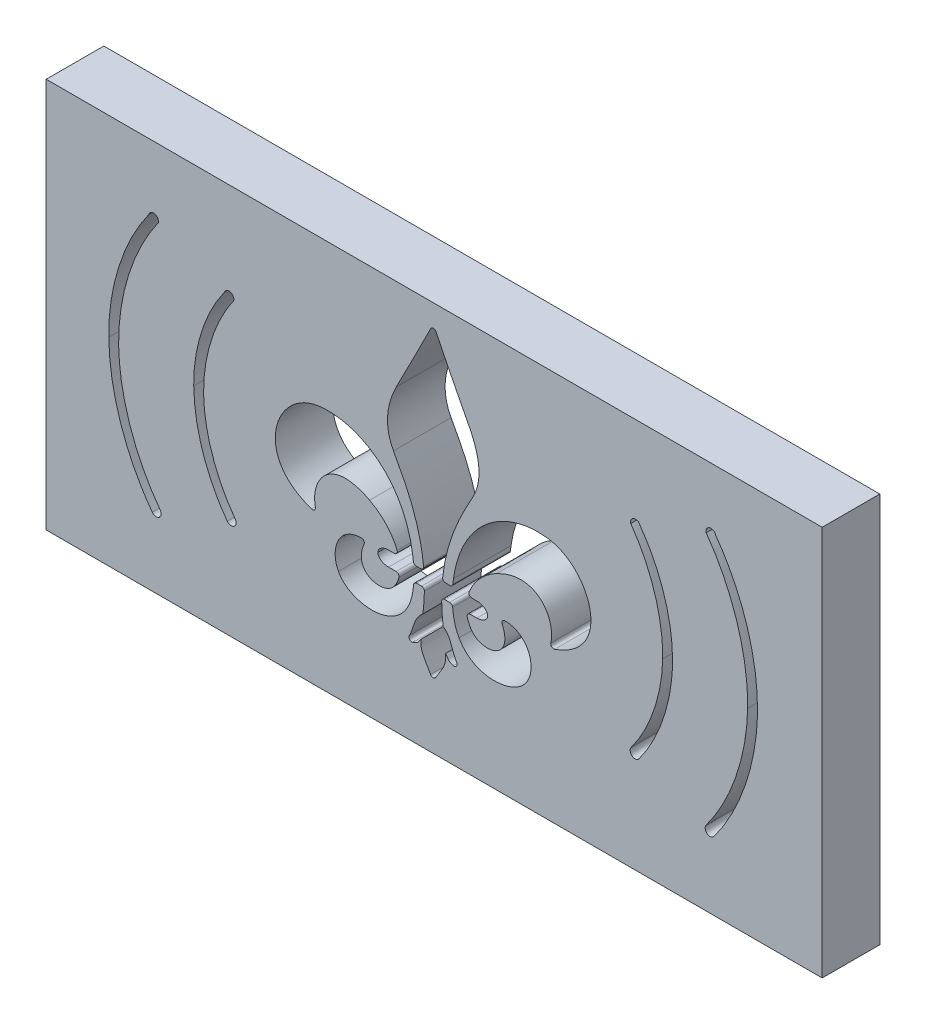
SolidWorks part; units mm, degrees
ref_plane "Front Plane" through (0, 0, 0) normal (0, 0, 1) x (1, 0, 0)
ref_plane "Top Plane" through (0, 0, 0) normal (0, 1, 0) x (1, 0, 0)
ref_plane "Right Plane" through (0, 0, 0) normal (1, 0, 0) x (0, 0, -1)
sketch "Model" plane through (0, 0, 0) normal (0, 0, 1) x (1, 0, 0)
  line L0 (91.0142, -254.4051) -> (92.3852, -254.4051)
  line L1 (95.3712, -254.4051) -> (96.8828, -254.4051)
  line L2 (96.8828, -251.3309) -> (95.641, -251.3309)
  line L3 (92.4284, -251.3309) -> (91.1584, -251.3309)
  line L4 (87.3892, -251.3309) -> (86.1192, -251.3309)
  line L5 (82.907, -251.3309) -> (81.5488, -251.3309)
  line L6 (81.5488, -254.4051) -> (83.1766, -254.4051)
  line L7 (86.1627, -254.4051) -> (87.51, -254.4051)
  arc A0 (53.3252, -261.3934) -> (55.1038, -260.0716) centre (54.2145, -260.7325) ccw
  arc A1 (54.8787, -227.6601) -> (52.7658, -226.9919) centre (53.8223, -227.326) ccw
  arc A2 (40.2952, -266.5598) -> (42.0738, -265.238) centre (41.1845, -265.8989) ccw
  arc A3 (41.7763, -222.4942) -> (39.6635, -221.826) centre (40.7199, -222.1601) ccw
  arc A4 (136.4853, -265.238) -> (138.264, -266.5598) centre (137.3746, -265.8989) ccw
  arc A5 (138.5846, -220.8425) -> (136.4718, -221.5108) centre (137.5282, -221.1766) ccw
  arc A6 (123.4553, -260.0716) -> (125.234, -261.3934) centre (124.3446, -260.7325) ccw
  arc A7 (125.4824, -226.0089) -> (123.3695, -226.6771) centre (124.426, -226.343) ccw
  spline S0 degree 3 poles (52.7658, -226.9919) (49.3239, -231.7614) (47.3715, -237.9346) (47.4449, -243.816) knots 0 0 0 0 1 1 1 1
  spline S1 degree 3 poles (47.4449, -243.816) (47.522, -249.9938) (49.64, -256.4345) (53.3252, -261.3934) knots 0 0 0 0 1.00991 1.00991 1.00991 1.00991
  spline S2 degree 3 poles (55.1038, -260.0716) (51.7573, -255.5684) (49.7728, -249.7523) (49.6658, -244.1428) knots 0 0 0 0 0.989781 0.989781 0.989781 0.989781
  spline S3 degree 3 poles (49.6658, -244.1428) (49.5938, -238.3808) (51.5066, -232.3329) (54.8787, -227.6601) knots 0 0 0 0 1 1 1 1
  spline S4 degree 3 poles (39.6635, -221.826) (35.1524, -228.077) (32.5936, -236.1676) (32.6898, -243.8758) knots 0 0 0 0 1 1 1 1
  spline S5 degree 3 poles (32.6898, -243.8758) (32.7894, -251.8502) (35.5383, -260.1588) (40.2952, -266.5598) knots 0 0 0 0 1.007595 1.007595 1.007595 1.007595
  spline S6 degree 3 poles (42.0738, -265.238) (37.6557, -259.2928) (35.0402, -251.609) (34.9105, -244.203) knots 0 0 0 0 0.992225 0.992225 0.992225 0.992225
  spline S7 degree 3 poles (34.9105, -244.203) (34.8158, -236.6141) (37.335, -228.6485) (41.7763, -222.4942) knots 0 0 0 0 1 1 1 1
  spline S8 degree 3 poles (87.51, -254.4051) (87.4975, -255.5745) (87.4217, -256.7951) (87.2653, -258.072) knots 0 0 0 0 1 1 1 1
  spline S9 degree 3 poles (87.2653, -258.072) (85.0539, -259.8873) (85.9452, -262.4287) (83.6838, -263.816) knots 0 0 0 0 1 1 1 1
  spline S10 degree 3 poles (83.6838, -263.816) (85.2333, -263.8568) (86.4972, -263.553) (86.9049, -262.9822) knots 0 0 0 0 1 1 1 1
  spline S11 degree 3 poles (86.9049, -262.9822) (86.9049, -264.3316) (88.3498, -266.0215) (89.2465, -268.0414) knots 0 0 0 0 1 1 1 1
  spline S12 degree 3 poles (89.2465, -268.0414) (90.2117, -266.0327) (91.6925, -264.6374) (91.6925, -262.9822) knots 0 0 0 0 1 1 1 1
  spline S13 degree 3 poles (91.6925, -262.9822) (92.1003, -263.553) (93.3643, -263.8568) (94.9136, -263.816) knots 0 0 0 0 1 1 1 1
  spline S14 degree 3 poles (94.9136, -263.816) (92.4473, -262.1979) (93.2063, -259.4913) (91.2591, -258.237) knots 0 0 0 0 1 1 1 1
  spline S15 degree 3 poles (91.2591, -258.237) (91.0959, -256.9032) (91.0221, -255.6264) (91.0142, -254.4051) knots 0 0 0 0 1 1 1 1
  spline S16 degree 3 poles (92.3852, -254.4051) (92.4986, -256.0206) (92.8495, -257.5657) (93.5485, -258.7993) knots 0 0 0 0 1 1 1 1
  spline S17 degree 3 poles (93.5485, -258.7993) (96.4633, -263.9429) (104.1659, -262.8624) (105.9293, -259.2579) knots 0 0 0 0 1 1 1 1
  spline S18 degree 3 poles (105.9293, -259.2579) (107.5338, -256.4306) (106.0582, -251.1916) (100.5052, -251.9225) knots 0 0 0 0 1 1 1 1
  spline S19 degree 3 poles (100.5052, -251.9225) (103.7908, -257.4239) (97.904, -258.7993) (96.1463, -256.2777) knots 0 0 0 0 1 1 1 1
  spline S20 degree 3 poles (96.1463, -256.2777) (95.7494, -255.7083) (95.4947, -255.0746) (95.3712, -254.4051) knots 0 0 0 0 1 1 1 1
  spline S21 degree 3 poles (96.8828, -254.4051) (98.0542, -254.4051) (99.0038, -253.717) (99.0038, -252.868) knots 0 0 0 0 1 1 1 1
  spline S22 degree 3 poles (99.0038, -252.868) (99.0038, -252.019) (98.0542, -251.3309) (96.8828, -251.3309) knots 0 0 0 0 1 1 1 1
  spline S23 degree 3 poles (95.641, -251.3309) (96.3355, -249.2549) (98.0146, -247.2301) (100.4252, -245.9626) knots 0 0 0 0 1 1 1 1
  spline S24 degree 3 poles (100.4252, -245.9626) (107.8374, -242.0656) (111.0464, -248.9425) (108.9833, -252.763) knots 0 0 0 0 1 1 1 1
  spline S25 degree 3 poles (108.9833, -252.763) (121.6673, -249.6302) (117.264, -236.6636) (109.0598, -235.7237) knots 0 0 0 0 1 1 1 1
  spline S26 degree 3 poles (109.0598, -235.7237) (101.7245, -234.8831) (94.0073, -240.0025) (92.5553, -250.2414) knots 0 0 0 0 1 1 1 1
  spline S27 degree 3 poles (92.5553, -250.2414) (92.5047, -250.5983) (92.4618, -250.9626) (92.4284, -251.3309) knots 0 0 0 0 1 1 1 1
  spline S28 degree 3 poles (91.1584, -251.3309) (91.8291, -244.4179) (94.7187, -239.5458) (96.4282, -236.3628) knots 0 0 0 0 1 1 1 1
  spline S29 degree 3 poles (96.4282, -236.3628) (98.6593, -232.2086) (96.8485, -228.1162) (95.9666, -226.285) knots 0 0 0 0 1 1 1 1
  spline S30 degree 3 poles (95.9666, -226.285) (94.9664, -224.208) (90.4692, -215.8124) (89.3154, -212.9661) knots 0 0 0 0 1 1 1 1
  spline S31 degree 3 poles (89.3154, -212.9661) (88.1615, -215.8124) (83.6304, -224.208) (82.6302, -226.285) knots 0 0 0 0 1 1 1 1
  spline S32 degree 3 poles (82.6302, -226.285) (81.7486, -228.1162) (79.9377, -232.2086) (82.1688, -236.3628) knots 0 0 0 0 1 1 1 1
  spline S33 degree 3 poles (82.1688, -236.3628) (83.8899, -239.5677) (86.7646, -244.3865) (87.3892, -251.3309) knots 0 0 0 0 1 1 1 1
  spline S34 degree 3 poles (86.1192, -251.3309) (86.0854, -250.9628) (86.0429, -250.5983) (85.9922, -250.2414) knots 0 0 0 0 1 1 1 1
  spline S35 degree 3 poles (85.9922, -250.2414) (84.5404, -240.0027) (76.8232, -234.8831) (69.4879, -235.7237) knots 0 0 0 0 1 1 1 1
  spline S36 degree 3 poles (69.4879, -235.7237) (61.2836, -236.6638) (56.8802, -249.6303) (69.5646, -252.763) knots 0 0 0 0 1 1 1 1
  spline S37 degree 3 poles (69.5646, -252.763) (67.5016, -248.9425) (70.7107, -242.0656) (78.1228, -245.9626) knots 0 0 0 0 1 1 1 1
  spline S38 degree 3 poles (78.1228, -245.9626) (80.5334, -247.2301) (82.2123, -249.2549) (82.907, -251.3309) knots 0 0 0 0 1 1 1 1
  spline S39 degree 3 poles (81.5488, -251.3309) (80.3774, -251.3309) (79.4277, -252.0189) (79.4277, -252.868) knots 0 0 0 0 1 1 1 1
  spline S40 degree 3 poles (79.4277, -252.868) (79.4277, -253.7169) (80.3774, -254.4051) (81.5488, -254.4051) knots 0 0 0 0 1 1 1 1
  spline S41 degree 3 poles (83.1766, -254.4051) (83.053, -255.0746) (82.7985, -255.7083) (82.4017, -256.2777) knots 0 0 0 0 1 1 1 1
  spline S42 degree 3 poles (82.4017, -256.2777) (80.6439, -258.7993) (74.757, -257.4239) (78.0427, -251.9225) knots 0 0 0 0 1 1 1 1
  spline S43 degree 3 poles (78.0427, -251.9225) (72.4897, -251.1916) (71.014, -256.4308) (72.6186, -259.2579) knots 0 0 0 0 1 1 1 1
  spline S44 degree 3 poles (72.6186, -259.2579) (74.3821, -262.8624) (82.0847, -263.9427) (84.9995, -258.7993) knots 0 0 0 0 1 1 1 1
  spline S45 degree 3 poles (84.9995, -258.7993) (85.6984, -257.5657) (86.0494, -256.0206) (86.1627, -254.4051) knots 0 0 0 0 1 1 1 1
  spline S46 degree 3 poles (136.4718, -221.5108) (141.1143, -227.9439) (143.7476, -236.2703) (143.6486, -244.203) knots 0 0 0 0 1 1 1 1
  spline S47 degree 3 poles (143.6486, -244.203) (143.5189, -251.609) (140.9034, -259.2928) (136.4853, -265.238) knots 0 0 0 0 0.992225 0.992225 0.992225 0.992225
  spline S48 degree 3 poles (138.264, -266.5598) (143.0208, -260.1588) (145.7697, -251.8502) (145.8693, -243.8758) knots 0 0 0 0 1.007595 1.007595 1.007595 1.007595
  spline S49 degree 3 poles (145.8693, -243.8758) (145.9699, -235.8238) (143.2969, -227.3724) (138.5846, -220.8425) knots 0 0 0 0 1 1 1 1
  spline S50 degree 3 poles (123.3695, -226.6771) (126.9428, -231.6285) (128.9696, -238.0371) (128.8933, -244.1428) knots 0 0 0 0 1 1 1 1
  spline S51 degree 3 poles (128.8933, -244.1428) (128.7863, -249.7523) (126.8018, -255.5685) (123.4553, -260.0716) knots 0 0 0 0 0.989781 0.989781 0.989781 0.989781
  spline S52 degree 3 poles (125.234, -261.3934) (128.9192, -256.4345) (131.0371, -249.9938) (131.1142, -243.816) knots 0 0 0 0 1.00991 1.00991 1.00991 1.00991
  spline S53 degree 3 poles (131.1142, -243.816) (131.1919, -237.591) (129.1255, -231.0571) (125.4824, -226.0089) knots 0 0 0 0 1 1 1 1
sketch "Sketch2" plane through (0, 0, 0) normal (0, 0, 1) x (1, 0, 0)
  line L16 (92.6603, -251.5849) -> (90.8785, -251.5849)
  line L17 (96.8828, -251.5849) -> (95.2881, -251.5849)
  line L18 (95.0661, -254.1511) -> (96.8828, -254.1511)
  line L19 (90.7586, -254.1511) -> (92.622, -254.1511)
  line L20 (85.9259, -254.1511) -> (87.7667, -254.1511)
  line L21 (81.5488, -254.1511) -> (83.4818, -254.1511)
  line L22 (83.2599, -251.5849) -> (81.5488, -251.5849)
  line L23 (87.667, -251.5849) -> (85.8874, -251.5849)
  line L24 (92.1977, -251.5849) -> (91.44, -251.5849)
  line L25 (96.8828, -251.5849) -> (96.0028, -251.5849)
  line L26 (95.6863, -254.1511) -> (96.8828, -254.1511)
  line L27 (91.2714, -254.1511) -> (92.1502, -254.1511)
  line L28 (86.3977, -254.1511) -> (87.2518, -254.1511)
  line L29 (81.5488, -254.1511) -> (82.8615, -254.1511)
  line L30 (82.5452, -251.5849) -> (81.5488, -251.5849)
  line L31 (87.1095, -251.5849) -> (86.3498, -251.5849)
  arc A6 (40.499, -266.4083) -> (41.8699, -265.3895) centre (41.1845, -265.8989) ccw
  arc A7 (41.5448, -222.381) -> (39.8949, -221.9393) centre (40.7199, -222.1601) ccw
  arc A8 (40.499, -266.4083) -> (41.8699, -265.3895) centre (41.1845, -265.8989) ccw
  arc A9 (41.5448, -222.381) -> (39.8949, -221.9393) centre (40.7199, -222.1601) ccw
  arc A12 (53.529, -261.2419) -> (54.8999, -260.2231) centre (54.2145, -260.7325) ccw
  arc A13 (54.6472, -227.5469) -> (52.9973, -227.1052) centre (53.8223, -227.326) ccw
  arc A14 (53.529, -261.2419) -> (54.8999, -260.2231) centre (54.2145, -260.7325) ccw
  arc A15 (54.6472, -227.5469) -> (52.9973, -227.1052) centre (53.8223, -227.326) ccw
  arc A18 (123.6592, -260.2231) -> (125.0301, -261.2419) centre (124.3446, -260.7325) ccw
  arc A19 (125.2509, -226.1222) -> (123.601, -226.5639) centre (124.426, -226.343) ccw
  arc A20 (123.6592, -260.2231) -> (125.0301, -261.2419) centre (124.3446, -260.7325) ccw
  arc A21 (125.2509, -226.1222) -> (123.601, -226.5639) centre (124.426, -226.343) ccw
  arc A22 (95.5293, -250.893) -> (96.0028, -251.5849) centre (96.0028, -251.0769) ccw
  arc A23 (95.6863, -254.1511) -> (95.1937, -254.7831) centre (95.6863, -254.6591) ccw
  arc A24 (136.6892, -265.3895) -> (138.0601, -266.4083) centre (137.3746, -265.8989) ccw
  arc A25 (138.3532, -220.9558) -> (136.7032, -221.3975) centre (137.5282, -221.1766) ccw
  arc A26 (136.6892, -265.3895) -> (138.0601, -266.4083) centre (137.3746, -265.8989) ccw
  arc A27 (138.3532, -220.9558) -> (136.7032, -221.3975) centre (137.5282, -221.1766) ccw
  arc A28 (83.3541, -254.7831) -> (82.8615, -254.1511) centre (82.8615, -254.6591) ccw
  arc A29 (82.5452, -251.5849) -> (83.0187, -250.893) centre (82.5452, -251.0769) ccw
  arc A30 (86.3977, -254.1511) -> (85.8915, -254.6168) centre (86.3977, -254.6591) ccw
  arc A31 (87.7597, -254.6683) -> (87.2518, -254.1511) centre (87.2518, -254.6591) ccw
  arc A32 (91.2714, -254.1511) -> (90.7634, -254.666) centre (91.2714, -254.6591) ccw
  arc A33 (92.6565, -254.6168) -> (92.1502, -254.1511) centre (92.1502, -254.6591) ccw
  arc A34 (92.1977, -251.5849) -> (92.7031, -251.1283) centre (92.1977, -251.0769) ccw
  arc A35 (90.9348, -251.0236) -> (91.44, -251.5849) centre (91.44, -251.0769) ccw
  arc A36 (87.1095, -251.5849) -> (87.615, -251.0271) centre (87.1095, -251.0769) ccw
  arc A37 (85.8444, -251.1285) -> (86.3498, -251.5849) centre (86.3498, -251.0769) ccw
  arc A38 (101.2577, -252.8217) -> (101.7401, -252.1109) centre (101.7234, -252.6186) cw
  arc A39 (110.3763, -252.0895) -> (109.7144, -251.5006) centre (110.2107, -251.6093) cw
  arc A40 (88.8552, -214.6187) -> (89.774, -214.6194) centre (89.3144, -214.8359) cw
  arc A41 (68.8326, -251.5) -> (68.1705, -252.0888) centre (68.3363, -251.6086) cw
  arc A42 (85.7355, -263.3627) -> (85.1563, -262.6275) centre (85.6011, -262.8728) cw
  arc A43 (93.3709, -262.5892) -> (92.7958, -263.3439) centre (92.9389, -262.8565) cw
  arc A44 (89.7105, -266.6793) -> (88.8332, -266.6599) centre (89.2776, -266.4137) cw
  arc A45 (76.8079, -252.1108) -> (77.2903, -252.8216) centre (76.8247, -252.6185) cw
  spline S17 degree 3 poles (2726.261, 1060.9952) (424.0603, -242.9813) (81.8774, -343.6096) (38.4268, -259.7201) (38.0224, -258.8596) (37.2804, -257.1147) (36.9423, -256.229) (36.3312, -254.4313) (36.0586, -253.5192) (35.585, -251.6885) (35.383, -250.7674) (19.6406, -163.1917) (309.9453, -26.0134) (2936.1622, 497.0434) knots -12.054909 -12.054909 -12.054909 -12.054909 0.25 0.25 0.375 0.375 0.5 0.5 0.625 0.625 0.75 0.75 12.434793 12.434793 12.434793 12.434793 only from (41.8699, -265.3895) to (34.6565, -244.2062)
  spline S18 degree 3 poles (2968.1073, 345.1303) (362.5256, -18.9048) (16.6102, -152.8658) (33.6825, -250.88) (33.8939, -251.8681) (34.3887, -253.8207) (34.6723, -254.7869) (35.3121, -256.6993) (35.6688, -257.6462) (36.4478, -259.4988) (36.8708, -260.4072) (77.7672, -340.0075) (382.9144, -276.9325) (2792.8591, 913.5332) knots -11.948646 -11.948646 -11.948646 -11.948646 0.25 0.25 0.375 0.375 0.5 0.5 0.625 0.625 0.75 0.75 11.804774 11.804774 11.804774 11.804774 only from (32.9438, -243.8726) to (40.499, -266.4083)
  spline S19 degree 3 poles (2759.2683, -1472.8542) (511.7035, -265.5767) (83.283, -133.3816) (36.4436, -227.8267) (36.0437, -228.7203) (35.3153, -230.5304) (34.986, -231.4487) (34.3968, -233.3114) (34.137, -234.2565) (33.6932, -236.1516) (33.5082, -237.1042) (20.1059, -324.1576) (306.51, -451.4239) (2954.3305, -903.1284) knots -13.105397 -13.105397 -13.105397 -13.105397 0.25 0.25 0.375 0.375 0.5 0.5 0.625 0.625 0.75 0.75 11.98675 11.98675 11.98675 11.98675 only from (39.8949, -221.9393) to (32.9438, -243.8726)
  spline S20 degree 3 poles (2985.8454, -750.402) (352.1606, -449.4359) (20.9281, -330.2829) (35.2208, -237.4415) (35.4067, -236.486) (35.8497, -234.5967) (36.107, -233.6612) (36.693, -231.8084) (37.0219, -230.8909) (37.7441, -229.0951) (38.138, -228.2141) (77.2842, -149.0756) (386.8699, -210.0522) (2812.4014, -1358.8251) knots -11.700324 -11.700324 -11.700324 -11.700324 0.25 0.25 0.375 0.375 0.5 0.5 0.625 0.625 0.75 0.75 12.076538 12.076538 12.076538 12.076538 only from (34.6565, -244.2062) to (41.5448, -222.381)
  spline S21 degree 3 poles (41.8699, -265.3895) (40.7351, -263.8624) (39.7377, -262.251) (38.4268, -259.7201) (38.0224, -258.8596) (37.2804, -257.1147) (36.9423, -256.229) (36.3312, -254.4313) (36.0586, -253.5192) (35.585, -251.6885) (35.383, -250.7674) (34.8831, -247.9866) (34.6899, -246.1096) (34.6565, -244.2062) knots 0 0 0 0 0.25 0.25 0.375 0.375 0.5 0.5 0.625 0.625 0.75 0.75 1 1 1 1
  spline S22 degree 3 poles (32.9438, -243.8726) (32.969, -245.8937) (33.163, -247.8975) (33.6825, -250.88) (33.8939, -251.8681) (34.3887, -253.8207) (34.6723, -254.7869) (35.3121, -256.6993) (35.6688, -257.6462) (36.4478, -259.4988) (36.8708, -260.4072) (38.2426, -263.0772) (39.2925, -264.7847) (40.499, -266.4083) knots 0 0 0 0 0.25 0.25 0.375 0.375 0.5 0.5 0.625 0.625 0.75 0.75 1 1 1 1
  spline S23 degree 3 poles (39.8949, -221.9393) (38.7491, -223.527) (37.7466, -225.1994) (36.4436, -227.8267) (36.0437, -228.7203) (35.3153, -230.5304) (34.986, -231.4487) (34.3968, -233.3114) (34.137, -234.2565) (33.6932, -236.1516) (33.5082, -237.1042) (33.0659, -239.9774) (32.9193, -241.9133) (32.9438, -243.8726) knots 0 0 0 0 0.25 0.25 0.375 0.375 0.5 0.5 0.625 0.625 0.75 0.75 1 1 1 1
  spline S24 degree 3 poles (34.6565, -244.2062) (34.6322, -242.2588) (34.777, -240.3247) (35.2208, -237.4415) (35.4067, -236.486) (35.8497, -234.5967) (36.107, -233.6612) (36.693, -231.8084) (37.0219, -230.8909) (37.7441, -229.0951) (38.138, -228.2141) (39.4199, -225.6226) (40.4065, -223.9628) (41.5448, -222.381) knots 0 0 0 0 0.25 0.25 0.375 0.375 0.5 0.5 0.625 0.625 0.75 0.75 1 1 1 1
  spline S29 degree 3 poles (2991.7715, 307.4824) (362.9641, -46.8254) (33.7094, -165.2692) (48.2674, -249.2306) (48.4302, -249.9949) (48.8113, -251.5049) (49.0298, -252.2521) (49.5228, -253.7309) (49.7979, -254.4636) (50.3991, -255.8972) (50.7256, -256.6001) (85.2726, -323.9703) (365.5807, -258.3425) (2789.5261, 959.6897) knots -13.279449 -13.279449 -13.279449 -13.279449 0.25 0.25 0.375 0.375 0.5 0.5 0.625 0.625 0.75 0.75 12.854743 12.854743 12.854743 12.854743 only from (47.6989, -243.8128) to (53.529, -261.2419)
  spline S30 degree 3 poles (2759.5859, -1508.6447) (533.1234, -300.5757) (92.0354, -147.6268) (50.3668, -231.5892) (50.0619, -232.2699) (49.5067, -233.6488) (49.2557, -234.3483) (48.8066, -235.7672) (48.6086, -236.4872) (48.2702, -237.9308) (48.1292, -238.6565) (36.845, -311.9009) (304.8668, -422.7216) (2979.102, -863.6805) knots -15.35936 -15.35936 -15.35936 -15.35936 0.25 0.25 0.375 0.375 0.5 0.5 0.625 0.625 0.75 0.75 13.173337 13.173337 13.173337 13.173337 only from (52.9973, -227.1052) to (47.6989, -243.8128)
  spline S31 degree 3 poles (3008.9721, -708.7247) (348.9759, -420.2737) (37.803, -317.2496) (49.8406, -239.0015) (49.9819, -238.2748) (50.3185, -236.838) (50.5141, -236.1265) (50.9594, -234.7175) (51.2095, -234.0197) (51.7584, -232.6539) (52.0578, -231.9838) (85.0054, -165.3316) (370.617, -229.3321) (2811.5372, -1400.8163) knots -13.007579 -13.007579 -13.007579 -13.007579 0.25 0.25 0.375 0.375 0.5 0.5 0.625 0.625 0.75 0.75 13.30549 13.30549 13.30549 13.30549 only from (49.4118, -244.1459) to (54.6472, -227.5469)
  spline S32 degree 3 poles (2721.2355, 1105.5818) (405.572, -224.583) (88.9621, -326.6599) (52.2852, -255.9202) (51.9779, -255.2671) (51.4139, -253.9429) (51.1567, -253.2708) (50.6919, -251.9064) (50.4844, -251.2143) (50.1236, -249.825) (49.9696, -249.1259) (36.5966, -175.1929) (310.6249, -54.1468) (2961.0633, 462.4521) knots -13.435922 -13.435922 -13.435922 -13.435922 0.25 0.25 0.375 0.375 0.5 0.5 0.625 0.625 0.75 0.75 13.761437 13.761437 13.761437 13.761437 only from (54.8999, -260.2231) to (49.4118, -244.1459)
  spline S33 degree 3 poles (47.6989, -243.8128) (47.7184, -245.3754) (47.8676, -246.9247) (48.2674, -249.2306) (48.4302, -249.9949) (48.8113, -251.5049) (49.0298, -252.2521) (49.5228, -253.7309) (49.7979, -254.4636) (50.3991, -255.8972) (50.7256, -256.6001) (51.785, -258.6659) (52.5961, -259.9866) (53.529, -261.2419) knots 0 0 0 0 0.25 0.25 0.375 0.375 0.5 0.5 0.625 0.625 0.75 0.75 1 1 1 1
  spline S34 degree 3 poles (52.9973, -227.1052) (52.1245, -228.3147) (51.3599, -229.5881) (50.3668, -231.5892) (50.0619, -232.2699) (49.5067, -233.6488) (49.2557, -234.3483) (48.8066, -235.7672) (48.6086, -236.4872) (48.2702, -237.9308) (48.1292, -238.6565) (47.792, -240.8454) (47.6803, -242.3202) (47.6989, -243.8128) knots 0 0 0 0 0.25 0.25 0.375 0.375 0.5 0.5 0.625 0.625 0.75 0.75 1 1 1 1
  spline S35 degree 3 poles (49.4118, -244.1459) (49.3933, -242.665) (49.5033, -241.1942) (49.8406, -239.0015) (49.9819, -238.2748) (50.3185, -236.838) (50.5141, -236.1265) (50.9594, -234.7175) (51.2095, -234.0197) (51.7584, -232.6539) (52.0578, -231.9838) (53.0321, -230.0127) (53.782, -228.7502) (54.6472, -227.5469) knots 0 0 0 0 0.25 0.25 0.375 0.375 0.5 0.5 0.625 0.625 0.75 0.75 1 1 1 1
  spline S36 degree 3 poles (54.8999, -260.2231) (54.0385, -259.064) (53.2811, -257.8409) (52.2852, -255.9202) (51.9779, -255.2671) (51.4139, -253.9429) (51.1567, -253.2708) (50.6919, -251.9064) (50.4844, -251.2143) (50.1236, -249.825) (49.9696, -249.1259) (49.5878, -247.0154) (49.4394, -245.5907) (49.4118, -244.1459) knots 0 0 0 0 0.25 0.25 0.375 0.375 0.5 0.5 0.625 0.625 0.75 0.75 1 1 1 1
  spline S79 degree 3 poles (-2547.8394, 1091.3487) (-213.1124, -235.366) (91.3398, -327.8707) (127.8441, -256.5784) (128.1726, -255.8694) (128.7733, -254.4326) (129.0462, -253.7035) (129.5379, -252.224) (129.7567, -251.4728) (130.1355, -249.9654) (130.2962, -249.2073) (143.944, -170.2263) (-143.4107, -45.1664) (-2784.1996, 446.2923) knots -12.457808 -12.457808 -12.457808 -12.457808 0.25 0.25 0.375 0.375 0.5 0.5 0.625 0.625 0.75 0.75 13.569896 13.569896 13.569896 13.569896 only from (125.0301, -261.2419) to (130.8602, -243.8128)
  spline S80 degree 3 poles (-2815.5378, 306.4146) (-171.1804, -57.4127) (142.8519, -170.5769) (128.5846, -249.1507) (128.4285, -249.8553) (128.0651, -251.2479) (127.8577, -251.9369) (127.3914, -253.3006) (127.1324, -253.9751) (126.5685, -255.2949) (126.263, -255.9422) (91.8723, -322.1674) (-195.2511, -251.7949) (-2611.6328, 962.5692) knots -13.467788 -13.467788 -13.467788 -13.467788 0.25 0.25 0.375 0.375 0.5 0.5 0.625 0.625 0.75 0.75 13.6736 13.6736 13.6736 13.6736 only from (129.1473, -244.1476) to (123.6592, -260.2231)
  spline S81 degree 3 poles (-2570.5463, -1536.19) (-230.0951, -251.8469) (89.9699, -157.5668) (126.3557, -231.288) (126.6749, -232.0043) (127.2562, -233.4555) (127.519, -234.1917) (127.9892, -235.6849) (128.1964, -236.4423) (128.5503, -237.9608) (128.6978, -238.7242) (140.398, -315.1241) (-135.8741, -430.2603) (-2799.9656, -873.0886) knots -12.743483 -12.743483 -12.743483 -12.743483 0.25 0.25 0.375 0.375 0.5 0.5 0.625 0.625 0.75 0.75 13.068669 13.068669 13.068669 13.068669 only from (123.601, -226.5639) to (129.1473, -244.1476)
  spline S82 degree 3 poles (-2826.1382, -722.769) (-167.9444, -425.2646) (142.8818, -319.0196) (130.4003, -238.3281) (130.2488, -237.5529) (129.888, -236.021) (129.6785, -235.2626) (129.2015, -233.7608) (128.9336, -233.0169) (128.3456, -231.5609) (128.0248, -230.8468) (89.0829, -152.4928) (-286.7055, -249.8081) (-2641.147, -1373.8411) knots -12.571925 -12.571925 -12.571925 -12.571925 0.25 0.25 0.375 0.375 0.5 0.5 0.625 0.625 0.75 0.75 14.616129 14.616129 14.616129 14.616129 only from (130.8602, -243.8128) to (125.2509, -226.1222)
  spline S83 degree 3 poles (125.0301, -261.2419) (125.9623, -259.9875) (126.7773, -258.6617) (127.8441, -256.5784) (128.1726, -255.8694) (128.7733, -254.4326) (129.0462, -253.7035) (129.5379, -252.224) (129.7567, -251.4728) (130.1355, -249.9654) (130.2962, -249.2073) (130.6915, -246.9193) (130.8407, -245.3761) (130.8602, -243.8128) knots 0 0 0 0 0.25 0.25 0.375 0.375 0.5 0.5 0.625 0.625 0.75 0.75 1 1 1 1
  spline S84 degree 3 poles (129.1473, -244.1476) (129.1197, -245.5914) (128.9711, -247.0222) (128.5846, -249.1507) (128.4285, -249.8553) (128.0651, -251.2479) (127.8577, -251.9369) (127.3914, -253.3006) (127.1324, -253.9751) (126.5685, -255.2949) (126.263, -255.9422) (125.2747, -257.8454) (124.5211, -259.0634) (123.6592, -260.2231) knots 0 0 0 0 0.25 0.25 0.375 0.375 0.5 0.5 0.625 0.625 0.75 0.75 1 1 1 1
  spline S85 degree 3 poles (123.601, -226.5639) (124.5171, -227.8376) (125.3156, -229.1806) (126.3557, -231.288) (126.6749, -232.0043) (127.2562, -233.4555) (127.519, -234.1917) (127.9892, -235.6849) (128.1964, -236.4423) (128.5503, -237.9608) (128.6978, -238.7242) (129.0504, -241.0266) (129.1669, -242.5778) (129.1473, -244.1476) knots 0 0 0 0 0.25 0.25 0.375 0.375 0.5 0.5 0.625 0.625 0.75 0.75 1 1 1 1
  spline S86 degree 3 poles (130.8602, -243.8128) (130.8799, -242.2334) (130.7618, -240.6653) (130.4003, -238.3281) (130.2488, -237.5529) (129.888, -236.021) (129.6785, -235.2626) (129.2015, -233.7608) (128.9336, -233.0169) (128.3456, -231.5609) (128.0248, -230.8468) (126.981, -228.7467) (126.1756, -227.4035) (125.2509, -226.1222) knots 0 0 0 0 0.25 0.25 0.375 0.375 0.5 0.5 0.625 0.625 0.75 0.75 1 1 1 1
  spline S91 degree 3 poles (-2551.33, 1049.7416) (-233.7829, -252.0557) (98.4075, -344.7746) (141.7024, -260.3783) (142.1281, -259.4618) (142.9067, -257.6043) (143.2606, -256.6617) (143.8985, -254.7488) (144.1824, -253.7776) (144.6741, -251.8288) (144.8828, -250.8485) (160.8835, -158.6571) (-140.6942, -17.7047) (-2758.2356, 486.2276) knots -11.37518 -11.37518 -11.37518 -11.37518 0.25 0.25 0.375 0.375 0.5 0.5 0.625 0.625 0.75 0.75 12.310992 12.310992 12.310992 12.310992 only from (138.0601, -266.4083) to (145.6153, -243.8726)
  spline S92 degree 3 poles (-2791.9552, 343.9962) (-173.3669, -28.2861) (159.9733, -157.6744) (143.1697, -250.7995) (142.965, -251.728) (142.488, -253.563) (142.2154, -254.471) (141.6025, -256.268) (141.2619, -257.1568) (140.5201, -258.8961) (140.118, -259.749) (99.3137, -338.4051) (-211.9827, -270.7674) (-2613.8671, 919.2904) knots -12.075946 -12.075946 -12.075946 -12.075946 0.25 0.25 0.375 0.375 0.5 0.5 0.625 0.625 0.75 0.75 12.386552 12.386552 12.386552 12.386552 only from (143.9026, -244.2075) to (136.6892, -265.3895)
  spline S93 degree 3 poles (-2573.4386, -1493.8046) (-247.1362, -233.2444) (97.4706, -140.8451) (140.2788, -227.5251) (140.693, -228.4544) (141.4476, -230.3369) (141.7887, -231.2918) (142.399, -233.2289) (142.6679, -234.2114) (143.1274, -236.1814) (143.3189, -237.1717) (157.0855, -326.9974) (-135.3925, -457.8891) (-2775.444, -911.3719) knots -11.515847 -11.515847 -11.515847 -11.515847 0.25 0.25 0.375 0.375 0.5 0.5 0.625 0.625 0.75 0.75 11.902802 11.902802 11.902802 11.902802 only from (136.7032, -221.3975) to (143.9026, -244.2075)
  spline S94 degree 3 poles (-2803.5027, -760.1739) (-171.7378, -453.7726) (159.7274, -331.8962) (145.0198, -236.7671) (144.8237, -235.7632) (144.3566, -233.7788) (144.0853, -232.7963) (143.4676, -230.8507) (143.1208, -229.8871) (142.3596, -228.0014) (141.9443, -227.0765) (97.7954, -138.1937) (-278.424, -222.164) (-2641.0673, -1333.3137) knots -11.405592 -11.405592 -11.405592 -11.405592 0.25 0.25 0.375 0.375 0.5 0.5 0.625 0.625 0.75 0.75 12.877759 12.877759 12.877759 12.877759 only from (145.6153, -243.8726) to (138.3532, -220.9558)
  spline S95 degree 3 poles (138.0601, -266.4083) (139.2657, -264.7859) (140.3207, -263.0717) (141.7024, -260.3783) (142.1281, -259.4618) (142.9067, -257.6043) (143.2606, -256.6617) (143.8985, -254.7488) (144.1824, -253.7776) (144.6741, -251.8288) (144.8828, -250.8485) (145.3962, -247.8901) (145.5901, -245.8946) (145.6153, -243.8726) knots 0 0 0 0 0.25 0.25 0.375 0.375 0.5 0.5 0.625 0.625 0.75 0.75 1 1 1 1
  spline S96 degree 3 poles (143.9026, -244.2075) (143.8693, -246.1096) (143.6758, -247.9948) (143.1697, -250.7995) (142.965, -251.728) (142.488, -253.563) (142.2154, -254.471) (141.6025, -256.268) (141.2619, -257.1568) (140.5201, -258.8961) (140.118, -259.749) (138.817, -262.2568) (137.8246, -263.8616) (136.6892, -265.3895) knots 0 0 0 0 0.25 0.25 0.375 0.375 0.5 0.5 0.625 0.625 0.75 0.75 1 1 1 1
  spline S97 degree 3 poles (136.7032, -221.3975) (137.8923, -223.0496) (138.9288, -224.7915) (140.2788, -227.5251) (140.693, -228.4544) (141.4476, -230.3369) (141.7887, -231.2918) (142.399, -233.2289) (142.6679, -234.2114) (143.1274, -236.1814) (143.3189, -237.1717) (143.7766, -240.1585) (143.928, -242.1708) (143.9026, -244.2075) knots 0 0 0 0 0.25 0.25 0.375 0.375 0.5 0.5 0.625 0.625 0.75 0.75 1 1 1 1
  spline S98 degree 3 poles (145.6153, -243.8726) (145.6409, -241.8268) (145.488, -239.7953) (145.0198, -236.7671) (144.8237, -235.7632) (144.3566, -233.7788) (144.0853, -232.7963) (143.4676, -230.8507) (143.1208, -229.8871) (142.3596, -228.0014) (141.9443, -227.0765) (140.5931, -224.3562) (139.551, -222.6157) (138.3532, -220.9558) knots 0 0 0 0 0.25 0.25 0.375 0.375 0.5 0.5 0.625 0.625 0.75 0.75 1 1 1 1
  spline S109 degree 3 poles (-2667.6518, 969.0749) (186.8917, -203.418) (93.9533, -199.2622) (82.1688, -227.9646) (82.0212, -228.3669) (81.7639, -229.1866) (81.655, -229.6016) (81.4844, -230.4351) (81.4224, -230.8547) (81.3514, -231.7007) (81.3424, -232.127) (81.3859, -232.9873) (81.4384, -233.4144) (81.6052, -234.2499) (81.7195, -234.6603) (91.8611, -262.7294) (252.709, -257.5926) (-1111.8238, 2512.1519) knots -8.803746 -8.803746 -8.803746 -8.803746 0.125 0.125 0.25 0.25 0.375 0.375 0.5 0.5 0.625 0.625 0.75 0.75 0.875 0.875 9.458349 9.458349 9.458349 9.458349 only from (82.8591, -226.3952) to (82.3925, -236.2426)
  spline S110 degree 3 poles (-2547.7326, 1214.1857) (105.5043, -140.3267) (104.8113, -181.6319) (88.2989, -215.7749) (88.0341, -216.3095) (87.2324, -217.9096) (86.6879, -218.9714) (85.5927, -221.0918) (85.0412, -222.1501) (84.2153, -223.7381) (83.94, -224.2675) (83.5298, -225.0629) (83.3935, -225.3282) (72.0224, -247.7029) (64.4748, -271.6999) (2718.3571, -1658.3797) knots -7.696481 -7.696481 -7.696481 -7.696481 0.125 0.125 0.25 0.25 0.5 0.5 0.75 0.75 0.875 0.875 0.9375 0.9375 6.133222 6.133222 6.133222 6.133222 only from (89.3152, -213.6154) to (82.8591, -226.3952)
  spline S111 degree 3 poles (-2537.7705, -1661.8949) (114.7006, -272.7395) (106.8099, -248.249) (95.2051, -225.3288) (95.0694, -225.0634) (94.6611, -224.2681) (94.3874, -223.7386) (93.566, -222.1504) (93.0178, -221.0919) (91.9289, -218.971) (91.3877, -217.909) (90.5903, -216.3088) (90.327, -215.7742) (73.7211, -181.272) (72.88, -139.6742) (2728.7293, 1209.6157) knots -5.262891 -5.262891 -5.262891 -5.262891 0.0625 0.0625 0.125 0.125 0.25 0.25 0.5 0.5 0.75 0.75 0.875 0.875 8.781291 8.781291 8.781291 8.781291 only from (95.7378, -226.3952) to (89.3152, -213.6154)
  spline S112 degree 3 poles (2833.5874, -1430.9172) (-1422.6551, 70.0636) (78.5446, -326.1772) (97.1578, -233.4206) (97.2108, -232.9892) (97.2545, -232.1349) (97.2461, -231.7085) (97.175, -230.857) (97.1118, -230.4297) (96.9388, -229.5878) (96.8297, -229.1747) (96.5737, -228.3613) (96.4268, -227.9611) (84.6099, -199.1946) (-10.4834, -199.4806) (2901.2647, 832.9552) knots -27.21608 -27.21608 -27.21608 -27.21608 0.25 0.25 0.375 0.375 0.5 0.5 0.625 0.625 0.75 0.75 0.875 0.875 9.855192 9.855192 9.855192 9.855192 only from (96.2044, -236.2426) to (95.7378, -226.3952)
  spline S113 degree 3 poles (-2875.3376, 193.338) (129.2492, -310.5481) (87.8104, -276.6185) (91.0278, -250.2277) (91.0748, -249.8901) (91.2328, -248.8804) (91.3609, -248.2112) (91.6622, -246.8808) (91.8357, -246.2185) (92.2244, -244.9101) (92.4395, -244.2634) (93.1429, -242.3441) (93.6919, -241.0905) (94.5951, -239.2526) (94.9093, -238.6467) (113.8737, -203.1138) (158.8764, -181.6761) (-2517.8135, 1232.9241) knots -4.746289 -4.746289 -4.746289 -4.746289 0.0625 0.0625 0.125 0.125 0.25 0.25 0.375 0.375 0.5 0.5 0.75 0.75 0.875 0.875 8.125282 8.125282 8.125282 8.125282 only from (90.8785, -251.5849) to (96.2044, -236.2426)
  spline S114 degree 3 poles (-701.218, -3135.0087) (359.8213, -161.7748) (100.5268, -190.3616) (92.7691, -250.5552) (92.7572, -250.648) (92.7458, -250.7408) (92.7351, -250.8337) (92.7243, -250.9266) (92.7142, -251.0196) (92.7046, -251.1127) (91.0143, -267.6099) (113.8651, -286.5452) (-2895.9948, 1.4434) knots -0.181794 -0.181794 -0.181794 -0.181794 0.000281 0.000281 0.000281 0.000561 0.000561 0.000561 0.000842 0.000842 0.000842 0.050593 0.050593 0.050593 0.050593 only from (92.8068, -250.2771) to (92.6603, -251.5849)
  spline S115 degree 3 poles (471.1185, -3211.2241) (263.7086, -695.5537) (171.5478, -228.8616) (105.5409, -236.0213) (105.0465, -236.1025) (104.0609, -236.3212) (103.5767, -236.4572) (102.1583, -236.9398) (101.2537, -237.3608) (99.9584, -238.1416) (99.5412, -238.4246) (98.7441, -239.0279) (98.3626, -239.3491) (97.6326, -240.0294) (97.2842, -240.3885) (96.6202, -241.1445) (96.306, -241.5404) (95.4289, -242.7593) (94.9249, -243.6207) (94.2793, -244.9794) (94.0821, -245.445) (93.7283, -246.3847) (93.5711, -246.8599) (71.0238, -324.7009) (518.9532, -529.4351) (-2849.233, 299.2833) knots -8.131384 -8.131384 -8.131384 -8.131384 0.125 0.125 0.1875 0.1875 0.25 0.25 0.375 0.375 0.4375 0.4375 0.5 0.5 0.5625 0.5625 0.625 0.625 0.75 0.75 0.8125 0.8125 0.875 0.875 10.946194 10.946194 10.946194 10.946194 only from (109.0309, -235.976) to (92.8068, -250.2771)
  spline S116 degree 3 poles (1188.2489, -3049.5368) (-73.2993, -53.7604) (71.9592, -272.4779) (112.4475, -251.1799) (112.665, -251.0565) (113.0925, -250.7931) (113.3029, -250.6528) (113.9118, -250.2111) (114.2914, -249.8872) (114.9888, -249.1699) (115.3081, -248.7724) (115.847, -247.9341) (116.0705, -247.4905) (116.3328, -246.786) (116.4083, -246.5431) (116.531, -246.0558) (116.5786, -245.8103) (116.6479, -245.3161) (116.6695, -245.0674) (116.6871, -244.5666) (116.6831, -244.3132) (116.6338, -243.5593) (116.5523, -243.0658) (116.3017, -242.0956) (116.1309, -241.6168) (115.7173, -240.7058) (115.4738, -240.2697) (115.0546, -239.6437) (114.9053, -239.4392) (114.593, -239.046) (114.4297, -238.8567) (113.9189, -238.3105) (113.5505, -237.975) (112.9537, -237.5169) (112.7464, -237.3712) (112.3232, -237.1004) (112.1072, -236.975) (111.4456, -236.6287) (110.9868, -236.4376) (83.12, -227.748) (-10.2388, -360.3178) (2735.4581, -1676.4116) knots -5.578257 -5.578257 -5.578257 -5.578257 0.125 0.125 0.15625 0.15625 0.1875 0.1875 0.25 0.25 0.3125 0.3125 0.375 0.375 0.40625 0.40625 0.4375 0.4375 0.46875 0.46875 0.5 0.5 0.5625 0.5625 0.625 0.625 0.6875 0.6875 0.71875 0.71875 0.75 0.75 0.8125 0.8125 0.84375 0.84375 0.875 0.875 0.9375 0.9375 4.520448 4.520448 4.520448 4.520448 only from (109.4438, -252.3794) to (109.0309, -235.976)
  spline S117 degree 3 poles (-943.7041, 2565.174) (98.1845, -481.142) (65.3521, -257.2805) (102.3478, -244.8838) (102.6511, -244.7979) (103.2692, -244.6604) (103.5854, -244.6086) (104.2256, -244.5495) (104.5448, -244.5424) (105.1812, -244.5795) (105.5009, -244.6244) (106.1261, -244.7721) (106.4274, -244.8736) (106.862, -245.0685) (107.004, -245.1405) (107.2819, -245.2994) (107.4186, -245.3868) (107.8114, -245.666) (108.0517, -245.8754) (108.4923, -246.3376) (108.6937, -246.5928) (109.0451, -247.1278) (109.1968, -247.4087) (109.4551, -247.9956) (109.5612, -248.3016) (109.7239, -248.9189) (109.7815, -249.2326) (109.8495, -249.8699) (109.8592, -250.1936) (109.8291, -250.8298) (109.7896, -251.145) (105.3369, -272.2673) (-19.9971, -287.2773) (-564.4995, 2667.9593) knots -7.552475 -7.552475 -7.552475 -7.552475 0.125 0.125 0.1875 0.1875 0.25 0.25 0.3125 0.3125 0.375 0.375 0.4375 0.4375 0.46875 0.46875 0.5 0.5 0.5625 0.5625 0.625 0.625 0.6875 0.6875 0.75 0.75 0.8125 0.8125 0.875 0.875 0.9375 0.9375 5.105224 5.105224 5.105224 5.105224 only from (100.3069, -245.7378) to (109.4438, -252.3794)
  spline S118 degree 3 poles (-2675.9583, 896.7402) (113.426, -286.9462) (91.1176, -263.3114) (95.5022, -250.9588) (95.5622, -250.8051) (95.7558, -250.3497) (95.9028, -250.0538) (96.3939, -249.1876) (96.7781, -248.6554) (97.4261, -247.9168) (97.6542, -247.6806) (98.1347, -247.2279) (98.3871, -247.0116) (201.5812, -166.4328) (1633.3834, -2015.3366) (-1249.3465, 2399.6924) knots -4.831328 -4.831328 -4.831328 -4.831328 0.0625 0.0625 0.125 0.125 0.25 0.25 0.5 0.5 0.625 0.625 0.75 0.75 50.265152 50.265152 50.265152 50.265152 only from (95.2881, -251.5849) to (100.3069, -245.7378)
  spline S119 degree 3 poles (-2459.1297, 1311.4651) (29.43, -324.1226) (103.7484, -259.2349) (98.482, -252.2041) (98.4099, -252.1299) (98.2515, -251.9958) (98.1647, -251.936) (97.8956, -251.7809) (97.6999, -251.7064) (73.2042, -245.7466) (-4.8686, -612.9427) (451.3462, 2726.6529) knots -10.100403 -10.100403 -10.100403 -10.100403 0.25 0.25 0.375 0.375 0.5 0.5 0.75 0.75 30.879865 30.879865 30.879865 30.879865 only from (98.7498, -252.868) to (96.8828, -251.5849)
  spline S120 degree 3 poles (484.2136, -3228.2619) (-15.8232, 135.2697) (72.2542, -260.2114) (97.6985, -254.0301) (97.8953, -253.9553) (98.2538, -253.7488) (98.4191, -253.6159) (98.6076, -253.3643) (98.6589, -253.2734) (101.7665, -244.7646) (-17.5745, -195.8855) (-1826.5257, -2550.1262) knots -31.144349 -31.144349 -31.144349 -31.144349 0.25 0.25 0.5 0.5 0.75 0.75 0.875 0.875 11.582634 11.582634 11.582634 11.582634 only from (96.8828, -254.1511) to (98.7498, -252.868)
  spline S121 degree 3 poles (-521.316, 2672.2349) (308.3573, -229.7779) (104.6241, -279.8961) (95.2953, -255.1474) (95.2348, -254.9513) (92.4542, -243.6142) (135.3339, -222.6661) (-2844.4242, -851.7866) knots -31.554987 -31.554987 -31.554987 -31.554987 0.5 0.5 0.75 0.75 14.768182 14.768182 14.768182 14.768182 only from (95.938, -256.423) to (95.0661, -254.1511)
  spline S122 degree 3 poles (2873.7111, 891.0862) (-73.6552, -262.6455) (92.7698, -227.8973) (101.5361, -253.5626) (101.5971, -253.7772) (101.6902, -254.2174) (101.7216, -254.4404) (101.7454, -254.8869) (101.7378, -255.1137) (101.674, -255.5579) (101.6187, -255.7731) (101.4552, -256.1877) (101.3447, -256.389) (101.0803, -256.7487) (100.9244, -256.9116) (100.5738, -257.1966) (100.384, -257.3156) (99.9784, -257.5117) (99.7647, -257.5876) (99.3298, -257.6959) (99.1048, -257.7293) (98.6565, -257.7545) (98.4331, -257.747) (97.9876, -257.6918) (97.7653, -257.6436) (97.3401, -257.5086) (97.1349, -257.4218) (96.7413, -257.2044) (96.5548, -257.0742) (84.1363, -246.0979) (155.0756, -124.2229) (2919.6982, -1259.3721) knots -7.435093 -7.435093 -7.435093 -7.435093 0.125 0.125 0.1875 0.1875 0.25 0.25 0.3125 0.3125 0.375 0.375 0.4375 0.4375 0.5 0.5 0.5625 0.5625 0.625 0.625 0.6875 0.6875 0.75 0.75 0.8125 0.8125 0.875 0.875 0.9375 0.9375 5.507284 5.507284 5.507284 5.507284 only from (100.9184, -252.1332) to (95.938, -256.423)
  spline S123 degree 3 poles (-2752.4736, 650.615) (-68.0458, -248.2896) (101.0292, -281.3172) (106.2152, -257.6972) (106.2481, -257.4768) (106.2854, -257.0387) (106.2901, -256.8195) (106.2725, -256.381) (106.25, -256.1603) (106.1774, -255.7248) (106.1278, -255.5113) (106.0017, -255.0932) (105.9252, -254.8885) (105.7431, -254.4886) (105.6365, -254.2921) (105.2804, -253.7386) (104.9932, -253.4106) (104.3078, -252.8461) (103.9277, -252.6255) (103.3118, -252.3809) (103.0995, -252.3143) (102.6733, -252.2107) (102.4578, -252.1731) (77.4334, -249.2628) (19.8888, -407.8053) (2571.9004, 1447.3345) knots -6.682565 -6.682565 -6.682565 -6.682565 0.125 0.125 0.1875 0.1875 0.25 0.25 0.3125 0.3125 0.375 0.375 0.4375 0.4375 0.5 0.5 0.625 0.625 0.75 0.75 0.8125 0.8125 0.875 0.875 7.998974 7.998974 7.998974 7.998974 only from (105.7046, -259.1392) to (100.9184, -252.1332)
  spline S124 degree 3 poles (-2335.7858, -2011.5549) (630.0995, 323.5) (53.8543, -218.999) (95.0404, -260.2876) (95.2664, -260.4843) (95.7372, -260.8396) (95.9833, -260.9998) (96.7517, -261.4303) (97.3103, -261.6515) (98.164, -261.8767) (98.4525, -261.9348) (99.037, -262.019) (99.3343, -262.0449) (100.2192, -262.0743) (100.8051, -262.0317) (101.6778, -261.8746) (101.968, -261.8061) (102.5331, -261.6389) (102.8096, -261.5399) (103.3496, -261.3085) (103.6131, -261.1761) (104.1244, -260.8716) (104.3676, -260.7021) (104.8214, -260.3251) (105.0342, -260.1153) (119.8788, -242.0082) (-25.0804, -115.7144) (-2336.451, 1482.083) knots -12.171671 -12.171671 -12.171671 -12.171671 0.125 0.125 0.1875 0.1875 0.25 0.25 0.375 0.375 0.4375 0.4375 0.5 0.5 0.625 0.625 0.6875 0.6875 0.75 0.75 0.8125 0.8125 0.875 0.875 0.9375 0.9375 5.798531 5.798531 5.798531 5.798531 only from (93.7695, -258.6741) to (105.7046, -259.1392)
  spline S125 degree 3 poles (-2897.3053, -496.4898) (123.4389, -219.0322) (91.1614, -238.528) (92.6853, -254.933) (92.7072, -255.1279) (92.7855, -255.7113) (92.8543, -256.0974) (99.1681, -283.0712) (203.1181, -288.835) (2394.3668, 1664.1225) knots -10.252802 -10.252802 -10.252802 -10.252802 0.125 0.125 0.25 0.25 0.5 0.5 17.901578 17.901578 17.901578 17.901578 only from (92.622, -254.1511) to (93.7695, -258.6741)
  spline S126 degree 3 poles (-2906.2083, -192.2214) (249.923, -356.3161) (94.2406, -311.6481) (90.8017, -255.9196) (90.7855, -255.5661) (89.923, -226.8686) (135.5009, -197.782) (-2908.2616, -218.1217) knots -38.699547 -38.699547 -38.699547 -38.699547 0.5 0.5 0.75 0.75 20.784749 20.784749 20.784749 20.784749 only from (91.0214, -258.3861) to (90.7586, -254.1511)
  spline S127 degree 3 poles (2553.8327, 1453.0062) (272.9564, -194.0421) (105.6951, -285.1714) (93.108, -262.1233) (93.0002, -261.8881) (92.8067, -261.4123) (92.7203, -261.1703) (92.4668, -260.4424) (92.3082, -259.9515) (92.0056, -259.3905) (91.9397, -259.281) (91.7931, -259.0694) (91.7114, -258.9664) (91.5354, -258.7759) (91.441, -258.688) (84.9397, -253.4945) (45.1373, -287.6039) (2017.3771, 2040.9432) knots -12.437003 -12.437003 -12.437003 -12.437003 0.25 0.25 0.375 0.375 0.5 0.5 0.75 0.75 0.8125 0.8125 0.875 0.875 0.9375 0.9375 4.91062 4.91062 4.91062 4.91062 only from (94.1629, -263.5536) to (91.0214, -258.3861)
  spline S128 degree 3 poles (-1652.7567, 2178.6533) (-1071.28, 1365.0316) (-489.7641, 551.2017) (91.7518, -262.6283) (91.8301, -262.7379) (91.8682, -262.7938) (91.9893, -262.9546) (92.0988, -263.0358) (92.3319, -263.173) (92.4547, -263.227) (92.8331, -263.3658) (93.0978, -263.4264) (116.1211, -267.2194) (158.6786, -141.7454) (-291.9318, -3235.1206) knots -927.893526 -927.893526 -927.893526 -927.893526 0.125 0.1875 0.1875 0.25 0.25 0.375 0.375 0.5 0.5 0.75 0.75 22.262826 22.262826 22.262826 22.262826 only from (91.4385, -262.1899) to (94.1629, -263.5536)
  spline S129 degree 3 poles (2618.5841, -1878.4005) (78.8351, -317.6063) (76.6179, -287.2041) (90.2649, -265.8022) (90.5332, -265.3964) (91.0184, -264.5542) (91.2373, -264.116) (91.3833, -263.5284) (91.406, -263.408) (91.4347, -263.1649) (91.4385, -263.0431) (91.4385, 737.31) (91.4385, 1737.5412) (91.4406, 2737.7982) knots -12.553527 -12.553527 -12.553527 -12.553527 0.25 0.25 0.5 0.5 0.75 0.75 0.8125 0.8125 0.875 0.875 513.758844 513.758844 513.758844 513.758844 only from (89.2561, -267.4638) to (91.4385, -262.1899)
  spline S130 degree 3 poles (87.1544, 2737.8055) (87.1589, 1737.5778) (87.1589, 737.338) (87.1589, -262.9611) (87.1584, -263.0205) (87.1651, -263.1385) (87.1713, -263.1971) (87.1971, -263.3723) (87.2236, -263.488) (87.3229, -263.833) (87.4149, -264.0602) (87.6173, -264.4994) (87.7288, -264.7138) (88.0762, -265.3506) (88.3244, -265.7667) (101.9175, -289.4254) (97.1037, -322.7465) (-2492.3927, -1790.5885) knots -526.605945 -526.605945 -526.605945 -526.605945 0.125 0.125 0.15625 0.15625 0.1875 0.1875 0.25 0.25 0.375 0.375 0.5 0.5 0.75 0.75 14.591877 14.591877 14.591877 14.591877 only from (87.1589, -262.1897) to (89.2561, -267.4638)
  spline S131 degree 3 poles (400.1355, -3245.4233) (23.8088, -143.4555) (62.7317, -267.207) (85.506, -263.425) (85.7679, -263.3646) (86.1428, -263.2269) (86.2663, -263.1725) (86.4391, -263.0709) (86.4944, -263.0338) (86.598, -262.95) (86.6471, -262.9025) (86.7286, -262.7949) (86.7665, -262.739) (86.845, -262.6291) (668.2108, 551.2672) (1249.5767, 1365.1636) (1830.9204, 2178.9707) knots -21.129261 -21.129261 -21.129261 -21.129261 0.25 0.25 0.5 0.5 0.625 0.625 0.6875 0.6875 0.75 0.75 0.8125 0.8125 0.875 926.832002 926.832002 926.832002 926.832002 only from (84.447, -263.5529) to (87.1589, -262.1897)
  spline S132 degree 3 poles (-2145.2, 1745.2598) (136.4166, -275.0842) (94.5489, -251.586) (87.1135, -258.5483) (87.023, -258.641) (86.7655, -258.9313) (86.6123, -259.141) (86.2063, -259.8175) (86.0236, -260.3057) (85.6955, -261.2954) (85.5475, -261.7974) (85.2282, -262.5056) (85.1056, -262.7341) (74.5503, -278.2813) (-56.0986, -224.3905) (818.2744, 2641.7723) knots -4.774125 -4.774125 -4.774125 -4.774125 0.0625 0.0625 0.125 0.125 0.25 0.25 0.5 0.5 0.75 0.75 0.875 0.875 9.703328 9.703328 9.703328 9.703328 only from (87.5051, -258.2038) to (84.447, -263.5529)
  spline S133 degree 3 poles (3086.9096, -247.903) (44.6949, -199.4174) (88.671, -227.7921) (87.7357, -255.5053) (87.7191, -255.8435) (84.1549, -311.0441) (-68.0884, -354.877) (3085.4237, -244.7199) knots -19.970325 -19.970325 -19.970325 -19.970325 0.25 0.25 0.5 0.5 41.086463 41.086463 41.086463 41.086463 only from (87.7667, -254.1511) to (87.5051, -258.2038)
  spline S134 degree 3 poles (-2264.0941, 1605.0281) (-24.6509, -287.9786) (79.3661, -283.1431) (85.694, -256.0958) (85.7627, -255.7093) (85.8408, -255.1272) (85.8627, -254.9327) (87.3857, -238.5385) (55.2228, -217.8805) (3065.5609, -600.1724) knots -16.934818 -16.934818 -16.934818 -16.934818 0.5 0.5 0.75 0.75 0.875 0.875 11.255041 11.255041 11.255041 11.255041 only from (84.7785, -258.6741) to (85.9259, -254.1511)
  spline S135 degree 3 poles (2418.667, 1610.0481) (178.1319, -125.9103) (59.71, -243.2508) (73.5095, -260.1106) (73.7227, -260.3215) (74.4067, -260.8907) (74.9178, -261.1878) (76.0102, -261.6568) (76.5742, -261.8207) (77.7318, -262.0303) (78.3297, -262.0741) (79.5037, -262.0353) (80.088, -261.9542) (81.2373, -261.652) (81.7839, -261.4361) (82.5572, -261.0045) (82.8086, -260.8411) (83.2798, -260.4858) (83.5012, -260.2932) (103.8527, -239.9571) (-2.383, -68.1477) (-1816.7032, -2572.2129) knots -4.50271 -4.50271 -4.50271 -4.50271 0.0625 0.0625 0.125 0.125 0.25 0.25 0.375 0.375 0.5 0.5 0.625 0.625 0.75 0.75 0.8125 0.8125 0.875 0.875 6.945006 6.945006 6.945006 6.945006 only from (72.8434, -259.1392) to (84.7785, -258.6741)
  spline S136 degree 3 poles (-125.6601, 2740.0843) (160.1006, -482.7654) (106.5565, -248.7104) (76.1072, -252.1705) (75.8928, -252.2072) (75.4667, -252.3091) (75.2534, -252.3751) (74.8433, -252.536) (74.6456, -252.6308) (74.2659, -252.8508) (74.0825, -252.9773) (73.5689, -253.3965) (73.2775, -253.7253) (72.7953, -254.4705) (72.6141, -254.8706) (72.3568, -255.7188) (72.285, -256.1533) (72.2577, -256.8135) (72.2624, -257.0364) (72.2995, -257.4745) (72.3317, -257.6909) (72.4247, -258.1179) (72.4855, -258.3285) (79.497, -277.1637) (219.168, -255.593) (240.0517, 2732.633) knots -8.639371 -8.639371 -8.639371 -8.639371 0.125 0.125 0.1875 0.1875 0.25 0.25 0.3125 0.3125 0.375 0.375 0.5 0.5 0.625 0.625 0.75 0.75 0.8125 0.8125 0.875 0.875 0.9375 0.9375 6.550312 6.550312 6.550312 6.550312 only from (77.6295, -252.1332) to (72.8434, -259.1392)
  spline S137 degree 3 poles (-1996.9997, 1905.204) (-53.6906, -60.6823) (98.3504, -242.5749) (81.9967, -257.0716) (81.8096, -257.2024) (81.418, -257.4194) (81.2112, -257.5075) (80.7811, -257.6442) (80.5624, -257.6914) (80.1185, -257.7467) (79.8911, -257.7545) (79.4444, -257.7294) (79.2241, -257.697) (78.7899, -257.5897) (78.5748, -257.5137) (78.1719, -257.32) (77.9806, -257.2011) (77.6293, -256.9172) (77.4746, -256.7567) (77.2086, -256.3978) (77.0974, -256.1973) (76.9317, -255.7816) (76.8746, -255.5613) (76.8103, -255.1166) (76.8025, -254.8935) (76.8257, -254.4463) (76.8571, -254.2213) (76.9491, -253.7841) (77.0096, -253.5698) (85.1593, -229.6216) (237.4974, -244.2379) (-2856.2701, -877.7078) knots -5.985533 -5.985533 -5.985533 -5.985533 0.0625 0.0625 0.125 0.125 0.1875 0.1875 0.25 0.25 0.3125 0.3125 0.375 0.375 0.4375 0.4375 0.5 0.5 0.5625 0.5625 0.625 0.625 0.6875 0.6875 0.75 0.75 0.8125 0.8125 0.875 0.875 7.910281 7.910281 7.910281 7.910281 only from (82.6101, -256.423) to (77.6295, -252.1332)
  spline S138 degree 3 poles (3013.6797, -896.3923) (43.269, -222.2355) (86.0981, -243.607) (83.3127, -254.9524) (83.2522, -255.1483) (73.3064, -281.5243) (-155.009, -218.5607) (556.9401, 2696.7459) knots -13.762437 -13.762437 -13.762437 -13.762437 0.25 0.25 0.5 0.5 34.680599 34.680599 34.680599 34.680599 only from (83.4818, -254.1511) to (82.6101, -256.423)
  spline S139 degree 3 poles (2638.8719, -1815.2236) (148.8848, -181.6566) (74.6851, -246.505) (79.9496, -253.5319) (80.0218, -253.6062) (80.1802, -253.7403) (80.267, -253.8001) (80.536, -253.9551) (80.7318, -254.0297) (105.2437, -259.9941) (183.4195, 107.7165) (-272.9587, -3232.3871) knots -10.095726 -10.095726 -10.095726 -10.095726 0.25 0.25 0.375 0.375 0.5 0.5 0.75 0.75 30.900428 30.900428 30.900428 30.900428 only from (79.6817, -252.868) to (81.5488, -254.1511)
  spline S140 degree 3 poles (-336.6562, 2718.2587) (206.462, -672.7008) (107.2099, -245.2837) (80.7343, -251.7056) (80.5368, -251.7806) (80.178, -251.987) (80.0125, -252.1202) (79.8244, -252.3711) (79.7727, -252.4625) (76.8673, -260.4114) (179.9261, -307.9615) (1833.0228, 2178.8141) knots -32.509243 -32.509243 -32.509243 -32.509243 0.25 0.25 0.5 0.5 0.75 0.75 0.875 0.875 10.888858 10.888858 10.888858 10.888858 only from (81.5488, -251.5849) to (79.6817, -252.868)
  spline S141 degree 3 poles (1456.6934, 2402.4302) (-835.5653, -1280.0116) (0.9247, -185.0805) (80.427, -247.2198) (80.9064, -247.6713) (81.5532, -248.4084) (81.757, -248.6645) (82.1396, -249.1989) (82.3192, -249.4788) (82.6457, -250.0548) (82.7924, -250.3502) (82.9858, -250.8052) (83.0458, -250.9588) (87.4297, -263.3066) (65.2725, -287.3056) (2837.9591, 934.602) knots -37.578873 -37.578873 -37.578873 -37.578873 0.25 0.25 0.5 0.5 0.625 0.625 0.75 0.75 0.875 0.875 0.9375 0.9375 5.830108 5.830108 5.830108 5.830108 only from (78.241, -245.7378) to (83.2599, -251.5849)
  spline S142 degree 3 poles (3021.2595, 276.6262) (305.2867, -264.5693) (70.2318, -282.1852) (68.6731, -249.8744) (68.7403, -249.2403) (68.9847, -248.3077) (69.0894, -248.0054) (69.3435, -247.4244) (69.4932, -247.1447) (69.8423, -246.609) (70.0422, -246.3539) (70.4778, -245.8928) (70.7154, -245.6836) (71.2329, -245.3108) (71.5145, -245.1475) (72.0942, -244.8834) (72.3954, -244.7802) (73.0194, -244.6292) (73.3388, -244.5827) (73.9759, -244.5425) (74.2968, -244.5484) (75.2576, -244.6336) (75.8763, -244.7766) (108.6416, -255.683) (99.8612, -435.7101) (-1060.2559, 2529.444) knots -6.036556 -6.036556 -6.036556 -6.036556 0.125 0.125 0.25 0.25 0.3125 0.3125 0.375 0.375 0.4375 0.4375 0.5 0.5 0.5625 0.5625 0.625 0.625 0.6875 0.6875 0.75 0.75 0.875 0.875 7.532587 7.532587 7.532587 7.532587 only from (69.1041, -252.3794) to (78.241, -245.7378)
  spline S143 degree 3 poles (1044.0436, -3071.8457) (252.4032, -549.869) (110.0092, -223.27) (67.8126, -236.3587) (67.578, -236.4435) (67.1153, -236.6347) (66.8861, -236.7419) (66.217, -237.0919) (65.7969, -237.3617) (65.2027, -237.8171) (65.0106, -237.9773) (64.6387, -238.3149) (64.4583, -238.4927) (63.9444, -239.0424) (63.6345, -239.4331) (63.2177, -240.0547) (63.0868, -240.2678) (62.8418, -240.7065) (62.7275, -240.9325) (62.4167, -241.6168) (62.2496, -242.0852) (62.0618, -242.807) (62.0097, -243.0509) (61.9282, -243.5454) (61.8987, -243.7977) (61.8482, -244.5493) (61.8637, -245.0461) (61.9645, -245.7844) (62.0111, -246.0294) (62.1317, -246.5169) (62.2063, -246.7604) (62.4665, -247.4673) (62.6892, -247.9136) (63.094, -248.5472) (63.2416, -248.7535) (63.5555, -249.1482) (63.7215, -249.3364) (64.2441, -249.8762) (64.6269, -250.204) (65.4428, -250.797) (65.869, -251.0577) (66.7503, -251.5224) (67.2054, -251.7264) (103.1507, -265.6086) (211.215, -143.1671) (-2873.9529, -829.599) knots -5.451163 -5.451163 -5.451163 -5.451163 0.0625 0.0625 0.09375 0.09375 0.125 0.125 0.1875 0.1875 0.21875 0.21875 0.25 0.25 0.3125 0.3125 0.34375 0.34375 0.375 0.375 0.4375 0.4375 0.46875 0.46875 0.5 0.5 0.5625 0.5625 0.59375 0.59375 0.625 0.625 0.6875 0.6875 0.71875 0.71875 0.75 0.75 0.8125 0.8125 0.875 0.875 0.9375 0.9375 5.684427 5.684427 5.684427 5.684427 only from (69.5168, -235.976) to (69.1041, -252.3794)
  spline S144 degree 3 poles (2994.0784, 448.187) (-427.6217, -606.5828) (109.7756, -332.6519) (84.8432, -246.3977) (84.4979, -245.4684) (83.859, -244.1151) (83.6256, -243.6705) (83.1149, -242.7975) (82.8416, -242.3758) (81.967, -241.1559) (81.3115, -240.4024) (80.2095, -239.3702) (79.821, -239.042) (79.0217, -238.4353) (78.6087, -238.1546) (77.7563, -237.6384) (77.3169, -237.4029) (76.4107, -236.9782) (75.9418, -236.7884) (74.5072, -236.2979) (73.532, -236.0803) (29.8504, -231.2533) (-60.8889, -429.064) (2874.3434, -1276.9838) knots -11.066685 -11.066685 -11.066685 -11.066685 0.125 0.125 0.25 0.25 0.3125 0.3125 0.375 0.375 0.5 0.5 0.5625 0.5625 0.625 0.625 0.6875 0.6875 0.75 0.75 0.875 0.875 6.243403 6.243403 6.243403 6.243403 only from (85.7407, -250.2771) to (69.5168, -235.976)
  spline S145 degree 3 poles (3076.7726, -24.2441) (77.3862, -286.2431) (87.4517, -268.2325) (85.8617, -251.3057) (85.853, -251.2126) (85.8437, -251.1196) (85.8338, -251.0266) (85.8238, -250.9337) (85.8133, -250.8408) (85.8023, -250.748) (79.8249, -200.7387) (-98.6122, -170.3289) (-2138.7838, -2253.9062) knots -0.050724 -0.050724 -0.050724 -0.050724 0.00028 0.00028 0.00028 0.000561 0.000561 0.000561 0.000841 0.000841 0.000841 0.151946 0.151946 0.151946 0.151946 only from (85.8874, -251.5849) to (85.7407, -250.2771)
  spline S146 degree 3 poles (2693.0199, 1239.0053) (20.4174, -182.105) (64.8535, -203.3963) (83.6879, -238.6451) (84.0023, -239.2506) (84.905, -241.0879) (85.4519, -242.3409) (86.1493, -244.2611) (86.362, -244.9084) (86.7448, -246.2187) (86.9146, -246.881) (87.2078, -248.2112) (87.3315, -248.8804) (87.4826, -249.8901) (87.5273, -250.2277) (90.5605, -276.616) (48.7892, -310.5396) (3053.9523, 191.4629) knots -7.071465 -7.071465 -7.071465 -7.071465 0.125 0.125 0.25 0.25 0.5 0.5 0.625 0.625 0.75 0.75 0.875 0.875 0.9375 0.9375 5.745802 5.745802 5.745802 5.745802 only from (82.3925, -236.2426) to (87.667, -251.5849)
  spline S147 degree 3 poles (82.8591, -226.3952) (82.6728, -226.7821) (82.4942, -227.172) (82.1688, -227.9646) (82.0212, -228.3669) (81.7639, -229.1866) (81.655, -229.6016) (81.4844, -230.4351) (81.4224, -230.8547) (81.3514, -231.7007) (81.3424, -232.127) (81.3859, -232.9873) (81.4384, -233.4144) (81.6052, -234.2499) (81.7195, -234.6603) (82.0106, -235.4661) (82.1882, -235.862) (82.3925, -236.2426) knots 0 0 0 0 0.125 0.125 0.25 0.25 0.375 0.375 0.5 0.5 0.625 0.625 0.75 0.75 0.875 0.875 1 1 1 1
  spline S148 degree 3 poles (88.8552, -214.6187) (88.7573, -214.8255) (88.6583, -215.0318) (88.2989, -215.7749) (88.0341, -216.3095) (87.2324, -217.9096) (86.6879, -218.9714) (85.5927, -221.0918) (85.0412, -222.1501) (84.2153, -223.7381) (83.94, -224.2675) (83.5298, -225.0629) (83.3935, -225.3282) (83.1232, -225.8601) (82.9886, -226.1264) (82.8591, -226.3952) knots 0.077055 0.077055 0.077055 0.077055 0.125 0.125 0.25 0.25 0.5 0.5 0.75 0.75 0.875 0.875 0.9375 0.9375 1 1 1 1
  spline S149 degree 3 poles (95.7378, -226.3952) (95.6084, -226.1266) (95.4743, -225.8605) (95.2051, -225.3288) (95.0694, -225.0634) (94.6611, -224.2681) (94.3874, -223.7386) (93.566, -222.1504) (93.0178, -221.0919) (91.9289, -218.971) (91.3877, -217.909) (90.5903, -216.3088) (90.327, -215.7742) (89.9696, -215.0317) (89.8712, -214.8258) (89.774, -214.6194) knots 0 0 0 0 0.0625 0.0625 0.125 0.125 0.25 0.25 0.5 0.5 0.75 0.75 0.875 0.875 0.92285 0.92285 0.92285 0.92285
  spline S150 degree 3 poles (96.2044, -236.2426) (96.6133, -235.4813) (96.9048, -234.6813) (97.1578, -233.4206) (97.2108, -232.9892) (97.2545, -232.1349) (97.2461, -231.7085) (97.175, -230.857) (97.1118, -230.4297) (96.9388, -229.5878) (96.8297, -229.1747) (96.5737, -228.3613) (96.4268, -227.9611) (96.1024, -227.1713) (95.924, -226.7819) (95.7378, -226.3952) knots 0 0 0 0 0.25 0.25 0.375 0.375 0.5 0.5 0.625 0.625 0.75 0.75 0.875 0.875 1 1 1 1
  spline S151 degree 3 poles (90.9348, -251.0236) (90.951, -250.871) (90.968, -250.7185) (91.0278, -250.2277) (91.0748, -249.8901) (91.2328, -248.8804) (91.3609, -248.2112) (91.6622, -246.8808) (91.8357, -246.2185) (92.2244, -244.9101) (92.4395, -244.2634) (93.1429, -242.3441) (93.6919, -241.0905) (94.5951, -239.2526) (94.9093, -238.6467) (95.5522, -237.4422) (95.8814, -236.844) (96.2044, -236.2426) knots 0.034411 0.034411 0.034411 0.034411 0.0625 0.0625 0.125 0.125 0.25 0.25 0.375 0.375 0.5 0.5 0.75 0.75 0.875 0.875 1 1 1 1
  spline S152 degree 3 poles (92.8068, -250.2771) (92.7937, -250.3697) (92.7811, -250.4624) (92.7691, -250.5552) (92.7572, -250.648) (92.7458, -250.7408) (92.7351, -250.8337) (92.7243, -250.9266) (92.7142, -251.0196) (92.7046, -251.1127) (92.7041, -251.1179) (92.7036, -251.1231) (92.7031, -251.1283) knots 0 0 0 0 0.000281 0.000281 0.000281 0.000561 0.000561 0.000561 0.000842 0.000842 0.000842 0.000857 0.000857 0.000857 0.000857
  spline S153 degree 3 poles (109.0309, -235.976) (108.0265, -235.8609) (107.0286, -235.8599) (105.5409, -236.0213) (105.0465, -236.1025) (104.0609, -236.3212) (103.5767, -236.4572) (102.1583, -236.9398) (101.2537, -237.3608) (99.9584, -238.1416) (99.5412, -238.4246) (98.7441, -239.0279) (98.3626, -239.3491) (97.6326, -240.0294) (97.2842, -240.3885) (96.6202, -241.1445) (96.306, -241.5404) (95.4289, -242.7593) (94.9249, -243.6207) (94.2793, -244.9794) (94.0821, -245.445) (93.7283, -246.3847) (93.5711, -246.8599) (93.1539, -248.3001) (92.9482, -249.2799) (92.8068, -250.2771) knots 0 0 0 0 0.125 0.125 0.1875 0.1875 0.25 0.25 0.375 0.375 0.4375 0.4375 0.5 0.5 0.5625 0.5625 0.625 0.625 0.75 0.75 0.8125 0.8125 0.875 0.875 1 1 1 1
  spline S154 degree 3 poles (110.3763, -252.0895) (111.0129, -251.87) (111.6314, -251.6092) (112.4475, -251.1799) (112.665, -251.0565) (113.0925, -250.7931) (113.3029, -250.6528) (113.9118, -250.2111) (114.2914, -249.8872) (114.9888, -249.1699) (115.3081, -248.7724) (115.847, -247.9341) (116.0705, -247.4905) (116.3328, -246.786) (116.4083, -246.5431) (116.531, -246.0558) (116.5786, -245.8103) (116.6479, -245.3161) (116.6695, -245.0674) (116.6871, -244.5666) (116.6831, -244.3132) (116.6338, -243.5593) (116.5523, -243.0658) (116.3017, -242.0956) (116.1309, -241.6168) (115.7173, -240.7058) (115.4738, -240.2697) (115.0546, -239.6437) (114.9053, -239.4392) (114.593, -239.046) (114.4297, -238.8567) (113.9189, -238.3105) (113.5505, -237.975) (112.9537, -237.5169) (112.7464, -237.3712) (112.3232, -237.1004) (112.1072, -236.975) (111.4456, -236.6287) (110.9868, -236.4376) (110.0312, -236.1396) (109.5334, -236.0336) (109.0309, -235.976) knots 0.040652 0.040652 0.040652 0.040652 0.125 0.125 0.15625 0.15625 0.1875 0.1875 0.25 0.25 0.3125 0.3125 0.375 0.375 0.40625 0.40625 0.4375 0.4375 0.46875 0.46875 0.5 0.5 0.5625 0.5625 0.625 0.625 0.6875 0.6875 0.71875 0.71875 0.75 0.75 0.8125 0.8125 0.84375 0.84375 0.875 0.875 0.9375 0.9375 1 1 1 1
  spline S155 degree 3 poles (100.3069, -245.7378) (100.8725, -245.4404) (101.4515, -245.1841) (102.3478, -244.8838) (102.6511, -244.7979) (103.2692, -244.6604) (103.5854, -244.6086) (104.2256, -244.5495) (104.5448, -244.5424) (105.1812, -244.5795) (105.5009, -244.6244) (106.1261, -244.7721) (106.4274, -244.8736) (106.862, -245.0685) (107.004, -245.1405) (107.2819, -245.2994) (107.4186, -245.3868) (107.8114, -245.666) (108.0517, -245.8754) (108.4923, -246.3376) (108.6937, -246.5928) (109.0451, -247.1278) (109.1968, -247.4087) (109.4551, -247.9956) (109.5612, -248.3016) (109.7239, -248.9189) (109.7815, -249.2326) (109.8495, -249.8699) (109.8592, -250.1936) (109.8291, -250.8298) (109.7896, -251.145) (109.7207, -251.4716) (109.7176, -251.4861) (109.7144, -251.5006) knots 0 0 0 0 0.125 0.125 0.1875 0.1875 0.25 0.25 0.3125 0.3125 0.375 0.375 0.4375 0.4375 0.46875 0.46875 0.5 0.5 0.5625 0.5625 0.625 0.625 0.6875 0.6875 0.75 0.75 0.8125 0.8125 0.875 0.875 0.9375 0.9375 0.940407 0.940407 0.940407 0.940407
  spline S156 degree 3 poles (95.5293, -250.893) (95.5605, -250.8126) (95.593, -250.7327) (95.7558, -250.3497) (95.9028, -250.0538) (96.3939, -249.1876) (96.7781, -248.6554) (97.4261, -247.9168) (97.6542, -247.6806) (98.1347, -247.2279) (98.3871, -247.0116) (99.1666, -246.4029) (99.7202, -246.0463) (100.3069, -245.7378) knots 0.09232 0.09232 0.09232 0.09232 0.125 0.125 0.25 0.25 0.5 0.5 0.625 0.625 0.75 0.75 1 1 1 1
  spline S157 degree 3 poles (98.7498, -252.868) (98.7498, -252.6574) (98.6705, -252.4558) (98.482, -252.2041) (98.4099, -252.1299) (98.2515, -251.9958) (98.1647, -251.936) (97.8956, -251.7809) (97.6999, -251.7064) (97.2967, -251.6083) (97.0914, -251.5849) (96.8828, -251.5849) knots 0 0 0 0 0.25 0.25 0.375 0.375 0.5 0.5 0.75 0.75 1 1 1 1
  spline S158 degree 3 poles (96.8828, -254.1511) (97.0914, -254.1511) (97.2964, -254.1278) (97.6985, -254.0301) (97.8953, -253.9553) (98.2538, -253.7488) (98.4191, -253.6159) (98.6076, -253.3643) (98.6589, -253.2734) (98.7307, -253.0771) (98.7498, -252.9734) (98.7498, -252.868) knots 0 0 0 0 0.25 0.25 0.5 0.5 0.75 0.75 0.875 0.875 1 1 1 1
  spline S159 degree 3 poles (95.938, -256.423) (95.7036, -256.0868) (95.5119, -255.722) (95.299, -255.1572) (95.241, -254.9713) (95.1937, -254.7831) knots 0 0 0 0 0.5 0.5 0.737229 0.737229 0.737229 0.737229
  spline S160 degree 3 poles (101.2577, -252.8217) (101.3337, -252.9958) (101.4029, -253.1725) (101.5361, -253.5626) (101.5971, -253.7772) (101.6902, -254.2174) (101.7216, -254.4404) (101.7454, -254.8869) (101.7378, -255.1137) (101.674, -255.5579) (101.6187, -255.7731) (101.4552, -256.1877) (101.3447, -256.389) (101.0803, -256.7487) (100.9244, -256.9116) (100.5738, -257.1966) (100.384, -257.3156) (99.9784, -257.5117) (99.7647, -257.5876) (99.3298, -257.6959) (99.1048, -257.7293) (98.6565, -257.7545) (98.4331, -257.747) (97.9876, -257.6918) (97.7653, -257.6436) (97.3401, -257.5086) (97.1349, -257.4218) (96.7413, -257.2044) (96.5548, -257.0742) (96.2197, -256.778) (96.0677, -256.6091) (95.938, -256.423) knots 0.071642 0.071642 0.071642 0.071642 0.125 0.125 0.1875 0.1875 0.25 0.25 0.3125 0.3125 0.375 0.375 0.4375 0.4375 0.5 0.5 0.5625 0.5625 0.625 0.625 0.6875 0.6875 0.75 0.75 0.8125 0.8125 0.875 0.875 0.9375 0.9375 1 1 1 1
  spline S161 degree 3 poles (105.7046, -259.1392) (105.924, -258.7525) (106.0737, -258.3418) (106.2152, -257.6972) (106.2481, -257.4768) (106.2854, -257.0387) (106.2901, -256.8195) (106.2725, -256.381) (106.25, -256.1603) (106.1774, -255.7248) (106.1278, -255.5113) (106.0017, -255.0932) (105.9252, -254.8885) (105.7431, -254.4886) (105.6365, -254.2921) (105.2804, -253.7386) (104.9932, -253.4106) (104.3078, -252.8461) (103.9277, -252.6255) (103.3118, -252.3809) (103.0995, -252.3143) (102.6733, -252.2107) (102.4578, -252.1731) (102.0747, -252.1285) (101.9077, -252.1164) (101.7401, -252.1109) knots 0 0 0 0 0.125 0.125 0.1875 0.1875 0.25 0.25 0.3125 0.3125 0.375 0.375 0.4375 0.4375 0.5 0.5 0.625 0.625 0.75 0.75 0.8125 0.8125 0.875 0.875 0.922527 0.922527 0.922527 0.922527
  spline S162 degree 3 poles (93.7695, -258.6741) (94.0628, -259.1918) (94.4156, -259.6612) (95.0404, -260.2876) (95.2664, -260.4843) (95.7372, -260.8396) (95.9833, -260.9998) (96.7517, -261.4303) (97.3103, -261.6515) (98.164, -261.8767) (98.4525, -261.9348) (99.037, -262.019) (99.3343, -262.0449) (100.2192, -262.0743) (100.8051, -262.0317) (101.6778, -261.8746) (101.968, -261.8061) (102.5331, -261.6389) (102.8096, -261.5399) (103.3496, -261.3085) (103.6131, -261.1761) (104.1244, -260.8716) (104.3676, -260.7021) (104.8214, -260.3251) (105.0342, -260.1153) (105.4111, -259.6556) (105.5732, -259.4078) (105.7046, -259.1392) knots 0 0 0 0 0.125 0.125 0.1875 0.1875 0.25 0.25 0.375 0.375 0.4375 0.4375 0.5 0.5 0.625 0.625 0.6875 0.6875 0.75 0.75 0.8125 0.8125 0.875 0.875 0.9375 0.9375 1 1 1 1
  spline S163 degree 3 poles (92.6565, -254.6168) (92.6599, -254.6571) (92.6634, -254.6975) (92.6853, -254.933) (92.7072, -255.1279) (92.7855, -255.7113) (92.8543, -256.0974) (93.1225, -257.2435) (93.3821, -257.9904) (93.7695, -258.6741) knots 0.099194 0.099194 0.099194 0.099194 0.125 0.125 0.25 0.25 0.5 0.5 1 1 1 1
  spline S164 degree 3 poles (91.0214, -258.3861) (90.9355, -257.6836) (90.8671, -256.979) (90.8017, -255.9196) (90.7855, -255.5661) (90.7694, -255.0303) (90.7659, -254.8482) (90.7634, -254.666) knots 0 0 0 0 0.5 0.5 0.75 0.75 0.878723 0.878723 0.878723 0.878723
  spline S165 degree 3 poles (93.3709, -262.5892) (93.3222, -262.5104) (93.2755, -262.43) (93.108, -262.1233) (93.0002, -261.8881) (92.8067, -261.4123) (92.7203, -261.1703) (92.4668, -260.4424) (92.3082, -259.9515) (92.0056, -259.3905) (91.9397, -259.281) (91.7931, -259.0694) (91.7114, -258.9664) (91.5354, -258.7759) (91.441, -258.688) (91.2396, -258.5272) (91.1307, -258.4564) (91.0214, -258.3861) knots 0.204504 0.204504 0.204504 0.204504 0.25 0.25 0.375 0.375 0.5 0.5 0.75 0.75 0.8125 0.8125 0.875 0.875 0.9375 0.9375 1 1 1 1
  spline S166 degree 3 poles (91.4385, -262.1899) (91.5168, -262.2995) (91.6343, -262.4639) (91.7518, -262.6283) (91.8301, -262.7379) (91.8682, -262.7938) (91.9893, -262.9546) (92.0988, -263.0358) (92.3319, -263.173) (92.4547, -263.227) (92.6516, -263.2992) (92.7234, -263.3226) (92.7958, -263.3439) knots 0 0 0 0 0.125 0.1875 0.1875 0.25 0.25 0.375 0.375 0.5 0.5 0.570123 0.570123 0.570123 0.570123
  spline S167 degree 3 poles (89.7105, -266.6793) (89.8067, -266.5227) (89.9047, -266.3671) (90.2649, -265.8022) (90.5332, -265.3964) (91.0184, -264.5542) (91.2373, -264.116) (91.3833, -263.5284) (91.406, -263.408) (91.4347, -263.1649) (91.4385, -263.0431) (91.4385, -262.6774) (91.4385, -262.4337) (91.4385, -262.1899) knots 0.155438 0.155438 0.155438 0.155438 0.25 0.25 0.5 0.5 0.75 0.75 0.8125 0.8125 0.875 0.875 1 1 1 1
  spline S168 degree 3 poles (87.1589, -262.1897) (87.1589, -262.427) (87.1589, -262.6644) (87.1589, -262.9611) (87.1584, -263.0205) (87.1651, -263.1385) (87.1713, -263.1971) (87.1971, -263.3723) (87.2236, -263.488) (87.3229, -263.833) (87.4149, -264.0602) (87.6173, -264.4994) (87.7288, -264.7138) (88.0762, -265.3506) (88.3244, -265.7667) (88.6558, -266.3436) (88.7453, -266.5013) (88.8332, -266.6599) knots 0 0 0 0 0.125 0.125 0.15625 0.15625 0.1875 0.1875 0.25 0.25 0.375 0.375 0.5 0.5 0.75 0.75 0.843642 0.843642 0.843642 0.843642
  spline S169 degree 3 poles (85.7355, -263.3627) (85.8309, -263.3366) (85.9252, -263.3068) (86.1428, -263.2269) (86.2663, -263.1725) (86.4391, -263.0709) (86.4944, -263.0338) (86.598, -262.95) (86.6471, -262.9025) (86.7286, -262.7949) (86.7665, -262.739) (86.845, -262.6291) (86.9627, -262.4643) (87.0804, -262.2995) (87.1589, -262.1897) knots 0.407312 0.407312 0.407312 0.407312 0.5 0.5 0.625 0.625 0.6875 0.6875 0.75 0.75 0.8125 0.8125 0.875 1 1 1 1
  spline S170 degree 3 poles (87.5051, -258.2038) (87.4038, -258.2869) (87.3032, -258.3707) (87.1135, -258.5483) (87.023, -258.641) (86.7655, -258.9313) (86.6123, -259.141) (86.2063, -259.8175) (86.0236, -260.3057) (85.6955, -261.2954) (85.5475, -261.7974) (85.2799, -262.391) (85.2208, -262.5105) (85.1563, -262.6275) knots 0 0 0 0 0.0625 0.0625 0.125 0.125 0.25 0.25 0.5 0.5 0.75 0.75 0.814329 0.814329 0.814329 0.814329
  spline S171 degree 3 poles (87.7597, -254.6683) (87.7567, -254.8345) (87.7528, -255.0007) (87.7357, -255.5053) (87.7191, -255.8435) (87.6536, -256.8573) (87.5874, -257.5315) (87.5051, -258.2038) knots 0.127281 0.127281 0.127281 0.127281 0.25 0.25 0.5 0.5 1 1 1 1
  spline S172 degree 3 poles (84.7785, -258.6741) (85.1663, -257.9896) (85.4256, -257.2428) (85.694, -256.0958) (85.7627, -255.7093) (85.8408, -255.1272) (85.8627, -254.9327) (85.8846, -254.6973) (85.8881, -254.6571) (85.8915, -254.6168) knots 0 0 0 0 0.5 0.5 0.75 0.75 0.875 0.875 0.900785 0.900785 0.900785 0.900785
  spline S173 degree 3 poles (72.8434, -259.1392) (72.9752, -259.4086) (73.1368, -259.6552) (73.5095, -260.1106) (73.7227, -260.3215) (74.4067, -260.8907) (74.9178, -261.1878) (76.0102, -261.6568) (76.5742, -261.8207) (77.7318, -262.0303) (78.3297, -262.0741) (79.5037, -262.0353) (80.088, -261.9542) (81.2373, -261.652) (81.7839, -261.4361) (82.5572, -261.0045) (82.8086, -260.8411) (83.2798, -260.4858) (83.5012, -260.2932) (84.1234, -259.6714) (84.4847, -259.1926) (84.7785, -258.6741) knots 0 0 0 0 0.0625 0.0625 0.125 0.125 0.25 0.25 0.375 0.375 0.5 0.5 0.625 0.625 0.75 0.75 0.8125 0.8125 0.875 0.875 1 1 1 1
  spline S174 degree 3 poles (76.8079, -252.1108) (76.6456, -252.1162) (76.4838, -252.1277) (76.1072, -252.1705) (75.8928, -252.2072) (75.4667, -252.3091) (75.2534, -252.3751) (74.8433, -252.536) (74.6456, -252.6308) (74.2659, -252.8508) (74.0825, -252.9773) (73.5689, -253.3965) (73.2775, -253.7253) (72.7953, -254.4705) (72.6141, -254.8706) (72.3568, -255.7188) (72.285, -256.1533) (72.2577, -256.8135) (72.2624, -257.0364) (72.2995, -257.4745) (72.3317, -257.6909) (72.4247, -258.1179) (72.4855, -258.3285) (72.6399, -258.7434) (72.7336, -258.9458) (72.8434, -259.1392) knots 0.078309 0.078309 0.078309 0.078309 0.125 0.125 0.1875 0.1875 0.25 0.25 0.3125 0.3125 0.375 0.375 0.5 0.5 0.625 0.625 0.75 0.75 0.8125 0.8125 0.875 0.875 0.9375 0.9375 1 1 1 1
  spline S175 degree 3 poles (82.6101, -256.423) (82.4805, -256.6088) (82.3312, -256.775) (81.9967, -257.0716) (81.8096, -257.2024) (81.418, -257.4194) (81.2112, -257.5075) (80.7811, -257.6442) (80.5624, -257.6914) (80.1185, -257.7467) (79.8911, -257.7545) (79.4444, -257.7294) (79.2241, -257.697) (78.7899, -257.5897) (78.5748, -257.5137) (78.1719, -257.32) (77.9806, -257.2011) (77.6293, -256.9172) (77.4746, -256.7567) (77.2086, -256.3978) (77.0974, -256.1973) (76.9317, -255.7816) (76.8746, -255.5613) (76.8103, -255.1166) (76.8025, -254.8935) (76.8257, -254.4463) (76.8571, -254.2213) (76.9491, -253.7841) (77.0096, -253.5698) (77.1431, -253.1775) (77.2133, -252.9983) (77.2903, -252.8216) knots 0 0 0 0 0.0625 0.0625 0.125 0.125 0.1875 0.1875 0.25 0.25 0.3125 0.3125 0.375 0.375 0.4375 0.4375 0.5 0.5 0.5625 0.5625 0.625 0.625 0.6875 0.6875 0.75 0.75 0.8125 0.8125 0.875 0.875 0.928771 0.928771 0.928771 0.928771
  spline S176 degree 3 poles (83.3541, -254.7831) (83.3066, -254.9718) (83.2486, -255.1578) (83.0355, -255.7228) (82.8444, -256.0868) (82.6101, -256.423) knots 0.262431 0.262431 0.262431 0.262431 0.5 0.5 1 1 1 1
  spline S177 degree 3 poles (79.6817, -252.868) (79.6817, -253.0787) (79.7611, -253.2802) (79.9496, -253.5319) (80.0218, -253.6062) (80.1802, -253.7403) (80.267, -253.8001) (80.536, -253.9551) (80.7318, -254.0297) (81.1349, -254.1278) (81.3402, -254.1511) (81.5488, -254.1511) knots 0 0 0 0 0.25 0.25 0.375 0.375 0.5 0.5 0.75 0.75 1 1 1 1
  spline S178 degree 3 poles (81.5488, -251.5849) (81.3401, -251.5849) (81.1354, -251.6083) (80.7343, -251.7056) (80.5368, -251.7806) (80.178, -251.987) (80.0125, -252.1202) (79.8244, -252.3711) (79.7727, -252.4625) (79.701, -252.6585) (79.6817, -252.7627) (79.6817, -252.868) knots 0 0 0 0 0.25 0.25 0.5 0.5 0.75 0.75 0.875 0.875 1 1 1 1
  spline S179 degree 3 poles (78.241, -245.7378) (78.828, -246.0464) (79.383, -246.4038) (80.427, -247.2198) (80.9064, -247.6713) (81.5532, -248.4084) (81.757, -248.6645) (82.1396, -249.1989) (82.3192, -249.4788) (82.6457, -250.0548) (82.7924, -250.3502) (82.955, -250.7328) (82.9875, -250.8126) (83.0187, -250.893) knots 0 0 0 0 0.25 0.25 0.5 0.5 0.625 0.625 0.75 0.75 0.875 0.875 0.907671 0.907671 0.907671 0.907671
  spline S180 degree 3 poles (68.8326, -251.5) (68.7621, -251.1781) (68.7201, -250.8502) (68.6731, -249.8744) (68.7403, -249.2403) (68.9847, -248.3077) (69.0894, -248.0054) (69.3435, -247.4244) (69.4932, -247.1447) (69.8423, -246.609) (70.0422, -246.3539) (70.4778, -245.8928) (70.7154, -245.6836) (71.2329, -245.3108) (71.5145, -245.1475) (72.0942, -244.8834) (72.3954, -244.7802) (73.0194, -244.6292) (73.3388, -244.5827) (73.9759, -244.5425) (74.2968, -244.5484) (75.2576, -244.6336) (75.8763, -244.7766) (77.084, -245.1786) (77.6734, -245.4393) (78.241, -245.7378) knots 0.060139 0.060139 0.060139 0.060139 0.125 0.125 0.25 0.25 0.3125 0.3125 0.375 0.375 0.4375 0.4375 0.5 0.5 0.5625 0.5625 0.625 0.625 0.6875 0.6875 0.75 0.75 0.875 0.875 1 1 1 1
  spline S181 degree 3 poles (69.5168, -235.976) (69.0145, -236.0336) (68.526, -236.1374) (67.8126, -236.3587) (67.578, -236.4435) (67.1153, -236.6347) (66.8861, -236.7419) (66.217, -237.0919) (65.7969, -237.3617) (65.2027, -237.8171) (65.0106, -237.9773) (64.6387, -238.3149) (64.4583, -238.4927) (63.9444, -239.0424) (63.6345, -239.4331) (63.2177, -240.0547) (63.0868, -240.2678) (62.8418, -240.7065) (62.7275, -240.9325) (62.4167, -241.6168) (62.2496, -242.0852) (62.0618, -242.807) (62.0097, -243.0509) (61.9282, -243.5454) (61.8987, -243.7977) (61.8482, -244.5493) (61.8637, -245.0461) (61.9645, -245.7844) (62.0111, -246.0294) (62.1317, -246.5169) (62.2063, -246.7604) (62.4665, -247.4673) (62.6892, -247.9136) (63.094, -248.5472) (63.2416, -248.7535) (63.5555, -249.1482) (63.7215, -249.3364) (64.2441, -249.8762) (64.6269, -250.204) (65.4428, -250.797) (65.869, -251.0577) (66.7503, -251.5224) (67.2054, -251.7264) (67.837, -251.9704) (68.0032, -252.031) (68.1705, -252.0888) knots 0 0 0 0 0.0625 0.0625 0.09375 0.09375 0.125 0.125 0.1875 0.1875 0.21875 0.21875 0.25 0.25 0.3125 0.3125 0.34375 0.34375 0.375 0.375 0.4375 0.4375 0.46875 0.46875 0.5 0.5 0.5625 0.5625 0.59375 0.59375 0.625 0.625 0.6875 0.6875 0.71875 0.71875 0.75 0.75 0.8125 0.8125 0.875 0.875 0.9375 0.9375 0.959517 0.959517 0.959517 0.959517
  spline S182 degree 3 poles (85.7407, -250.2771) (85.5993, -249.2794) (85.394, -248.3032) (84.8432, -246.3977) (84.4979, -245.4684) (83.859, -244.1151) (83.6256, -243.6705) (83.1149, -242.7975) (82.8416, -242.3758) (81.967, -241.1559) (81.3115, -240.4024) (80.2095, -239.3702) (79.821, -239.042) (79.0217, -238.4353) (78.6087, -238.1546) (77.7563, -237.6384) (77.3169, -237.4029) (76.4107, -236.9782) (75.9418, -236.7884) (74.5072, -236.2979) (73.532, -236.0803) (71.544, -235.8606) (70.524, -235.8606) (69.5168, -235.976) knots 0 0 0 0 0.125 0.125 0.25 0.25 0.3125 0.3125 0.375 0.375 0.5 0.5 0.5625 0.5625 0.625 0.625 0.6875 0.6875 0.75 0.75 0.875 0.875 1 1 1 1
  spline S183 degree 3 poles (85.8444, -251.1285) (85.8409, -251.0945) (85.8374, -251.0606) (85.8338, -251.0266) (85.8238, -250.9337) (85.8133, -250.8408) (85.8023, -250.748) (85.7835, -250.5908) (85.763, -250.4338) (85.7407, -250.2771) knots 0.000458 0.000458 0.000458 0.000458 0.000561 0.000561 0.000561 0.000841 0.000841 0.000841 0.001316 0.001316 0.001316 0.001316
  spline S184 degree 3 poles (82.3925, -236.2426) (82.7154, -236.8437) (83.0448, -237.4415) (83.6879, -238.6451) (84.0023, -239.2506) (84.905, -241.0879) (85.4519, -242.3409) (86.1493, -244.2611) (86.362, -244.9084) (86.7448, -246.2187) (86.9146, -246.881) (87.2078, -248.2112) (87.3315, -248.8804) (87.4826, -249.8901) (87.5273, -250.2277) (87.5838, -250.7197) (87.5999, -250.8733) (87.615, -251.0271) knots 0 0 0 0 0.125 0.125 0.25 0.25 0.5 0.5 0.625 0.625 0.75 0.75 0.875 0.875 0.9375 0.9375 0.965807 0.965807 0.965807 0.965807
  dimension "D6" = 0.508
  dimension "D1" = 0.254
  dimension "D2" = 0.254
  dimension "D3" = 0.254
  dimension "D4" = 0.254
  dimension "D5" = 0.254
sketch "Sketch3" plane through (0, 0, 0) normal (0, 0, 1) x (1, 0, 0)
  line L1 (22.0815, -210.5014) -> (156.8517, -210.5014)
  line L2 (22.0815, -210.5014) -> (22.0815, -278.2973)
  line L3 (22.0815, -278.2973) -> (156.8517, -278.2973)
  line L4 (156.8517, -210.5014) -> (156.8517, -278.2973)
extrude "Boss-Extrude1" add sketch "Sketch3" along normal blind 10
extrude "Cut-Extrude1" cut sketch "Sketch2" along normal blind 10
